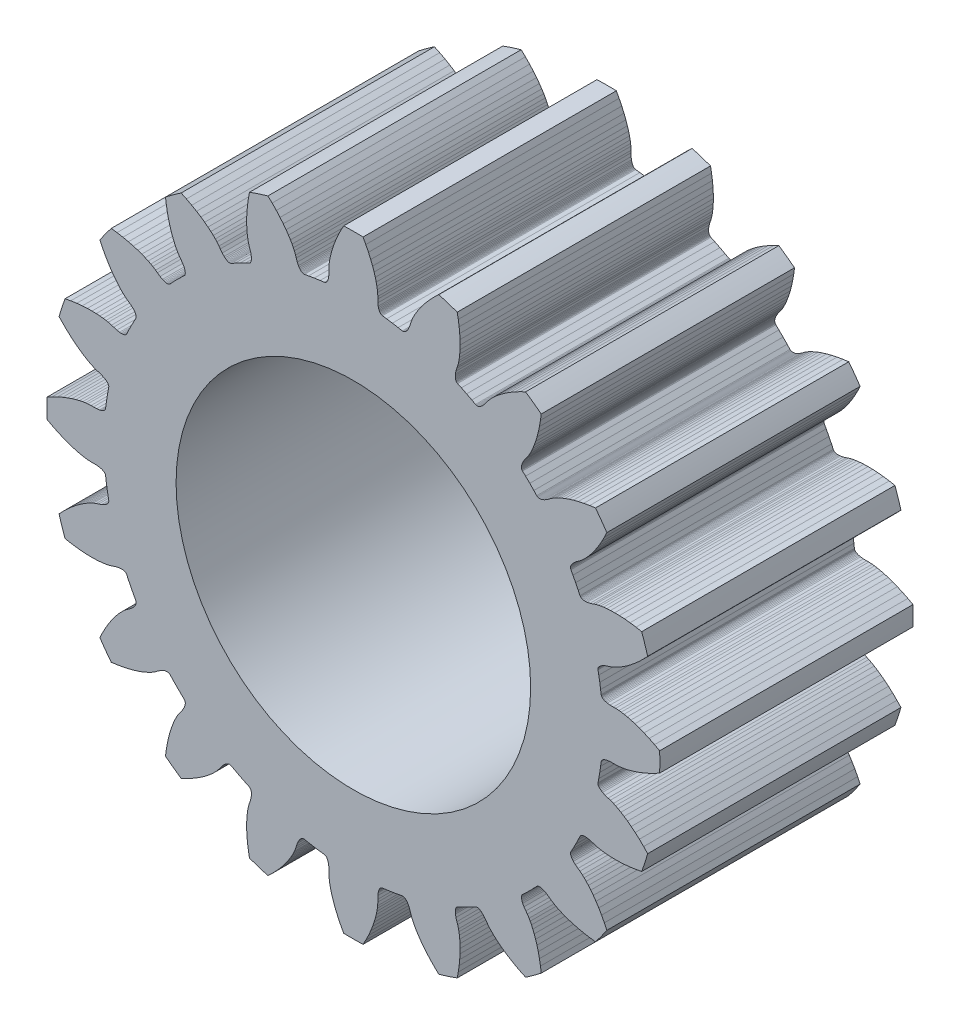
SolidWorks part; units mm, degrees
ref_plane "Front Plane" through (0, 0, 0) normal (0, 0, 1) x (1, 0, 0)
ref_plane "Top Plane" through (0, 0, 0) normal (0, 1, 0) x (1, 0, 0)
ref_plane "Right Plane" through (0, 0, 0) normal (1, 0, 0) x (0, 0, -1)
sketch "Model" plane through (0, 0, 0) normal (0, 0, 1) x (1, 0, 0)
  line L0 (11.4619, 3.2074) -> (11.2915, 3.0419)
  line L1 (11.2915, 3.0419) -> (11.1273, 2.8952)
  line L2 (11.1273, 2.8952) -> (10.9714, 2.7672)
  line L3 (10.9714, 2.7672) -> (10.8244, 2.6566)
  line L4 (10.8244, 2.6566) -> (10.6885, 2.5629)
  line L5 (10.6885, 2.5629) -> (10.5634, 2.4842)
  line L6 (10.5634, 2.4842) -> (10.4513, 2.42)
  line L7 (10.4513, 2.42) -> (10.3515, 2.3683)
  line L8 (10.3515, 2.3683) -> (10.268, 2.3294)
  line L9 (10.268, 2.3294) -> (10.146, 2.2812)
  line L10 (10.146, 2.2812) -> (10.0579, 2.255)
  line L11 (10.0579, 2.255) -> (9.9378, 2.2137)
  line L12 (9.9378, 2.2137) -> (9.8388, 2.1672)
  line L13 (9.8388, 2.1672) -> (9.7973, 2.1425)
  line L14 (9.7973, 2.1425) -> (9.7611, 2.117)
  line L15 (9.7611, 2.117) -> (9.7303, 2.0911)
  line L16 (9.7303, 2.0911) -> (9.7049, 2.065)
  line L17 (9.7049, 2.065) -> (9.6848, 2.0388)
  line L18 (9.6848, 2.0388) -> (9.67, 2.0128)
  line L19 (9.67, 2.0128) -> (9.6606, 1.9871)
  line L20 (9.6606, 1.9871) -> (9.6565, 1.962)
  line L21 (9.6565, 1.962) -> (9.6587, 1.9318)
  line L22 (9.6587, 1.9318) -> (9.6899, 1.7686)
  line L23 (9.6899, 1.7686) -> (9.7287, 1.5409)
  line L24 (9.7287, 1.5409) -> (9.7622, 1.3123)
  line L25 (9.7622, 1.3123) -> (9.7829, 1.1474)
  line L26 (9.7829, 1.1474) -> (9.7901, 1.118)
  line L27 (9.7901, 1.118) -> (9.8018, 1.0954)
  line L28 (9.8018, 1.0954) -> (9.8187, 1.0739)
  line L29 (9.8187, 1.0739) -> (9.8408, 1.0537)
  line L30 (9.8408, 1.0537) -> (9.868, 1.035)
  line L31 (9.868, 1.035) -> (9.9003, 1.018)
  line L32 (9.9003, 1.018) -> (9.9376, 1.0029)
  line L33 (9.9376, 1.0029) -> (9.9798, 0.9899)
  line L34 (9.9798, 0.9899) -> (10.0269, 0.9792)
  line L35 (10.0269, 0.9792) -> (10.1355, 0.9655)
  line L36 (10.1355, 0.9655) -> (10.2625, 0.9634)
  line L37 (10.2625, 0.9634) -> (10.3543, 0.9657)
  line L38 (10.3543, 0.9657) -> (10.4853, 0.9576)
  line L39 (10.4853, 0.9576) -> (10.5767, 0.9464)
  line L40 (10.5767, 0.9464) -> (10.6876, 0.9281)
  line L41 (10.6876, 0.9281) -> (10.814, 0.9017)
  line L42 (10.814, 0.9017) -> (10.9573, 0.8655)
  line L43 (10.9573, 0.8655) -> (11.1155, 0.8184)
  line L44 (11.1155, 0.8184) -> (11.2895, 0.7586)
  line L45 (11.2895, 0.7586) -> (11.4774, 0.685)
  line L46 (11.4774, 0.685) -> (11.6789, 0.5963)
  line L47 (11.6789, 0.5963) -> (11.8921, 0.4915)
  line L48 (11.8921, 0.4915) -> (12.094, 0.382)
  line L49 (12.094, -0.382) -> (11.8921, -0.4915)
  line L50 (11.8921, -0.4915) -> (11.6789, -0.5963)
  line L51 (11.6789, -0.5963) -> (11.4774, -0.685)
  line L52 (11.4774, -0.685) -> (11.2895, -0.7586)
  line L53 (11.2895, -0.7586) -> (11.1155, -0.8184)
  line L54 (11.1155, -0.8184) -> (10.9573, -0.8655)
  line L55 (10.9573, -0.8655) -> (10.814, -0.9017)
  line L56 (10.814, -0.9017) -> (10.6876, -0.9281)
  line L57 (10.6876, -0.9281) -> (10.5767, -0.9464)
  line L58 (10.5767, -0.9464) -> (10.4853, -0.9576)
  line L59 (10.4853, -0.9576) -> (10.3543, -0.9657)
  line L60 (10.3543, -0.9657) -> (10.2625, -0.9634)
  line L61 (10.2625, -0.9634) -> (10.1355, -0.9655)
  line L62 (10.1355, -0.9655) -> (10.0269, -0.9792)
  line L63 (10.0269, -0.9792) -> (9.9798, -0.9899)
  line L64 (9.9798, -0.9899) -> (9.9376, -1.0029)
  line L65 (9.9376, -1.0029) -> (9.9003, -1.018)
  line L66 (9.9003, -1.018) -> (9.868, -1.035)
  line L67 (9.868, -1.035) -> (9.8408, -1.0537)
  line L68 (9.8408, -1.0537) -> (9.8187, -1.0739)
  line L69 (9.8187, -1.0739) -> (9.8018, -1.0954)
  line L70 (9.8018, -1.0954) -> (9.7901, -1.118)
  line L71 (9.7901, -1.118) -> (9.7829, -1.1474)
  line L72 (9.7829, -1.1474) -> (9.7622, -1.3123)
  line L73 (9.7622, -1.3123) -> (9.7287, -1.5409)
  line L74 (9.7287, -1.5409) -> (9.6899, -1.7686)
  line L75 (9.6899, -1.7686) -> (9.6587, -1.9318)
  line L76 (9.6587, -1.9318) -> (9.6565, -1.962)
  line L77 (9.6565, -1.962) -> (9.6606, -1.9871)
  line L78 (9.6606, -1.9871) -> (9.67, -2.0128)
  line L79 (9.67, -2.0128) -> (9.6848, -2.0388)
  line L80 (9.6848, -2.0388) -> (9.7049, -2.065)
  line L81 (9.7049, -2.065) -> (9.7303, -2.0911)
  line L82 (9.7303, -2.0911) -> (9.7611, -2.117)
  line L83 (9.7611, -2.117) -> (9.7973, -2.1425)
  line L84 (9.7973, -2.1425) -> (9.8388, -2.1672)
  line L85 (9.8388, -2.1672) -> (9.9378, -2.2137)
  line L86 (9.9378, -2.2137) -> (10.0579, -2.255)
  line L87 (10.0579, -2.255) -> (10.146, -2.2812)
  line L88 (10.146, -2.2812) -> (10.268, -2.3294)
  line L89 (10.268, -2.3294) -> (10.3515, -2.3683)
  line L90 (10.3515, -2.3683) -> (10.4513, -2.42)
  line L91 (10.4513, -2.42) -> (10.5634, -2.4842)
  line L92 (10.5634, -2.4842) -> (10.6885, -2.5629)
  line L93 (10.6885, -2.5629) -> (10.8244, -2.6566)
  line L94 (10.8244, -2.6566) -> (10.9714, -2.7672)
  line L95 (10.9714, -2.7672) -> (11.1273, -2.8952)
  line L96 (11.1273, -2.8952) -> (11.2915, -3.0419)
  line L97 (11.2915, -3.0419) -> (11.4619, -3.2074)
  line L98 (11.4619, -3.2074) -> (11.6201, -3.374)
  line L99 (11.384, -4.1005) -> (11.1581, -4.1423)
  line L100 (11.1581, -4.1423) -> (10.923, -4.1761)
  line L101 (10.923, -4.1761) -> (10.7039, -4.1982)
  line L102 (10.7039, -4.1982) -> (10.5026, -4.2101)
  line L103 (10.5026, -4.2101) -> (10.3186, -4.2132)
  line L104 (10.3186, -4.2132) -> (10.1535, -4.2091)
  line L105 (10.1535, -4.2091) -> (10.0061, -4.1993)
  line L106 (10.0061, -4.1993) -> (9.8778, -4.1853)
  line L107 (9.8778, -4.1853) -> (9.7666, -4.1684)
  line L108 (9.7666, -4.1684) -> (9.6762, -4.1508)
  line L109 (9.6762, -4.1508) -> (9.5491, -4.1181)
  line L110 (9.5491, -4.1181) -> (9.4625, -4.0876)
  line L111 (9.4625, -4.0876) -> (9.3411, -4.0503)
  line L112 (9.3411, -4.0503) -> (9.2336, -4.0298)
  line L113 (9.2336, -4.0298) -> (9.1855, -4.0254)
  line L114 (9.1855, -4.0254) -> (9.1413, -4.0247)
  line L115 (9.1413, -4.0247) -> (9.1011, -4.0276)
  line L116 (9.1011, -4.0276) -> (9.0652, -4.0338)
  line L117 (9.0652, -4.0338) -> (9.0335, -4.0431)
  line L118 (9.0335, -4.0431) -> (9.0063, -4.0555)
  line L119 (9.0063, -4.0555) -> (8.9836, -4.0708)
  line L120 (8.9836, -4.0708) -> (8.9655, -4.0886)
  line L121 (8.9655, -4.0886) -> (8.9496, -4.1144)
  line L122 (8.9496, -4.1144) -> (8.8789, -4.2648)
  line L123 (8.8789, -4.2648) -> (8.7764, -4.4718)
  line L124 (8.7764, -4.4718) -> (8.6692, -4.6764)
  line L125 (8.6692, -4.6764) -> (8.589, -4.822)
  line L126 (8.589, -4.822) -> (8.5775, -4.85)
  line L127 (8.5775, -4.85) -> (8.5737, -4.8751)
  line L128 (8.5737, -4.8751) -> (8.5747, -4.9024)
  line L129 (8.5747, -4.9024) -> (8.5807, -4.9318)
  line L130 (8.5807, -4.9318) -> (8.5917, -4.9629)
  line L131 (8.5917, -4.9629) -> (8.6079, -4.9956)
  line L132 (8.6079, -4.9956) -> (8.6292, -5.0298)
  line L133 (8.6292, -5.0298) -> (8.6557, -5.0651)
  line L134 (8.6557, -5.0651) -> (8.6875, -5.1015)
  line L135 (8.6875, -5.1015) -> (8.7673, -5.1763)
  line L136 (8.7673, -5.1763) -> (8.8688, -5.2527)
  line L137 (8.8688, -5.2527) -> (8.9445, -5.3048)
  line L138 (8.9445, -5.3048) -> (9.0456, -5.3884)
  line L139 (9.0456, -5.3884) -> (9.113, -5.4512)
  line L140 (9.113, -5.4512) -> (9.192, -5.5312)
  line L141 (9.192, -5.5312) -> (9.2787, -5.6269)
  line L142 (9.2787, -5.6269) -> (9.3734, -5.7403)
  line L143 (9.3734, -5.7403) -> (9.4737, -5.8715)
  line L144 (9.4737, -5.8715) -> (9.5793, -6.0221)
  line L145 (9.5793, -6.0221) -> (9.688, -6.192)
  line L146 (9.688, -6.192) -> (9.7989, -6.3823)
  line L147 (9.7989, -6.3823) -> (9.9098, -6.5923)
  line L148 (9.9098, -6.5923) -> (10.0087, -6.7996)
  line L149 (9.5597, -7.4177) -> (9.332, -7.3876)
  line L150 (9.332, -7.3876) -> (9.0979, -7.3471)
  line L151 (9.0979, -7.3471) -> (8.8827, -7.3004)
  line L152 (8.8827, -7.3004) -> (8.6875, -7.2495)
  line L153 (8.6875, -7.2495) -> (8.5116, -7.1956)
  line L154 (8.5116, -7.1956) -> (8.3559, -7.1407)
  line L155 (8.3559, -7.1407) -> (8.2187, -7.0858)
  line L156 (8.2187, -7.0858) -> (8.101, -7.0329)
  line L157 (8.101, -7.0329) -> (8.0005, -6.9825)
  line L158 (8.0005, -6.9825) -> (7.9199, -6.9378)
  line L159 (7.9199, -6.9378) -> (7.8092, -6.8674)
  line L160 (7.8092, -6.8674) -> (7.7362, -6.8116)
  line L161 (7.7362, -6.8116) -> (7.6322, -6.7386)
  line L162 (7.6322, -6.7386) -> (7.5364, -6.6859)
  line L163 (7.5364, -6.6859) -> (7.492, -6.6669)
  line L164 (7.492, -6.6669) -> (7.4502, -6.6525)
  line L165 (7.4502, -6.6525) -> (7.4111, -6.6428)
  line L166 (7.4111, -6.6428) -> (7.375, -6.6376)
  line L167 (7.375, -6.6376) -> (7.342, -6.6368)
  line L168 (7.342, -6.6368) -> (7.3122, -6.6401)
  line L169 (7.3122, -6.6401) -> (7.286, -6.6476)
  line L170 (7.286, -6.6476) -> (7.2632, -6.659)
  line L171 (7.2632, -6.659) -> (7.2401, -6.6786)
  line L172 (7.2401, -6.6786) -> (7.1264, -6.7998)
  line L173 (7.1264, -6.7998) -> (6.965, -6.965)
  line L174 (6.965, -6.965) -> (6.7998, -7.1264)
  line L175 (6.7998, -7.1264) -> (6.6786, -7.2401)
  line L176 (6.6786, -7.2401) -> (6.659, -7.2632)
  line L177 (6.659, -7.2632) -> (6.6476, -7.286)
  line L178 (6.6476, -7.286) -> (6.6401, -7.3122)
  line L179 (6.6401, -7.3122) -> (6.6368, -7.342)
  line L180 (6.6368, -7.342) -> (6.6376, -7.375)
  line L181 (6.6376, -7.375) -> (6.6428, -7.4111)
  line L182 (6.6428, -7.4111) -> (6.6525, -7.4502)
  line L183 (6.6525, -7.4502) -> (6.6669, -7.492)
  line L184 (6.6669, -7.492) -> (6.6859, -7.5364)
  line L185 (6.6859, -7.5364) -> (6.7386, -7.6322)
  line L186 (6.7386, -7.6322) -> (6.8116, -7.7362)
  line L187 (6.8116, -7.7362) -> (6.8674, -7.8092)
  line L188 (6.8674, -7.8092) -> (6.9378, -7.9199)
  line L189 (6.9378, -7.9199) -> (6.9825, -8.0005)
  line L190 (6.9825, -8.0005) -> (7.0329, -8.101)
  line L191 (7.0329, -8.101) -> (7.0858, -8.2187)
  line L192 (7.0858, -8.2187) -> (7.1407, -8.3559)
  line L193 (7.1407, -8.3559) -> (7.1956, -8.5116)
  line L194 (7.1956, -8.5116) -> (7.2495, -8.6875)
  line L195 (7.2495, -8.6875) -> (7.3004, -8.8827)
  line L196 (7.3004, -8.8827) -> (7.3471, -9.0979)
  line L197 (7.3471, -9.0979) -> (7.3876, -9.332)
  line L198 (7.3876, -9.332) -> (7.4177, -9.5597)
  line L199 (6.7996, -10.0087) -> (6.5923, -9.9098)
  line L200 (6.5923, -9.9098) -> (6.3823, -9.7989)
  line L201 (6.3823, -9.7989) -> (6.192, -9.688)
  line L202 (6.192, -9.688) -> (6.0221, -9.5793)
  line L203 (6.0221, -9.5793) -> (5.8715, -9.4737)
  line L204 (5.8715, -9.4737) -> (5.7403, -9.3734)
  line L205 (5.7403, -9.3734) -> (5.6269, -9.2787)
  line L206 (5.6269, -9.2787) -> (5.5312, -9.192)
  line L207 (5.5312, -9.192) -> (5.4512, -9.113)
  line L208 (5.4512, -9.113) -> (5.3884, -9.0456)
  line L209 (5.3884, -9.0456) -> (5.3048, -8.9445)
  line L210 (5.3048, -8.9445) -> (5.2527, -8.8688)
  line L211 (5.2527, -8.8688) -> (5.1763, -8.7673)
  line L212 (5.1763, -8.7673) -> (5.1015, -8.6875)
  line L213 (5.1015, -8.6875) -> (5.0651, -8.6557)
  line L214 (5.0651, -8.6557) -> (5.0298, -8.6292)
  line L215 (5.0298, -8.6292) -> (4.9956, -8.6079)
  line L216 (4.9956, -8.6079) -> (4.9629, -8.5917)
  line L217 (4.9629, -8.5917) -> (4.9318, -8.5807)
  line L218 (4.9318, -8.5807) -> (4.9024, -8.5747)
  line L219 (4.9024, -8.5747) -> (4.8751, -8.5737)
  line L220 (4.8751, -8.5737) -> (4.85, -8.5775)
  line L221 (4.85, -8.5775) -> (4.822, -8.589)
  line L222 (4.822, -8.589) -> (4.6764, -8.6692)
  line L223 (4.6764, -8.6692) -> (4.4718, -8.7764)
  line L224 (4.4718, -8.7764) -> (4.2648, -8.8789)
  line L225 (4.2648, -8.8789) -> (4.1144, -8.9496)
  line L226 (4.1144, -8.9496) -> (4.0886, -8.9655)
  line L227 (4.0886, -8.9655) -> (4.0708, -8.9836)
  line L228 (4.0708, -8.9836) -> (4.0555, -9.0063)
  line L229 (4.0555, -9.0063) -> (4.0431, -9.0335)
  line L230 (4.0431, -9.0335) -> (4.0338, -9.0652)
  line L231 (4.0338, -9.0652) -> (4.0276, -9.1011)
  line L232 (4.0276, -9.1011) -> (4.0247, -9.1413)
  line L233 (4.0247, -9.1413) -> (4.0254, -9.1855)
  line L234 (4.0254, -9.1855) -> (4.0298, -9.2336)
  line L235 (4.0298, -9.2336) -> (4.0503, -9.3411)
  line L236 (4.0503, -9.3411) -> (4.0876, -9.4625)
  line L237 (4.0876, -9.4625) -> (4.1181, -9.5491)
  line L238 (4.1181, -9.5491) -> (4.1508, -9.6762)
  line L239 (4.1508, -9.6762) -> (4.1684, -9.7666)
  line L240 (4.1684, -9.7666) -> (4.1853, -9.8778)
  line L241 (4.1853, -9.8778) -> (4.1993, -10.0061)
  line L242 (4.1993, -10.0061) -> (4.2091, -10.1535)
  line L243 (4.2091, -10.1535) -> (4.2132, -10.3186)
  line L244 (4.2132, -10.3186) -> (4.2101, -10.5026)
  line L245 (4.2101, -10.5026) -> (4.1982, -10.7039)
  line L246 (4.1982, -10.7039) -> (4.1761, -10.923)
  line L247 (4.1761, -10.923) -> (4.1423, -11.1581)
  line L248 (4.1423, -11.1581) -> (4.1005, -11.384)
  line L249 (3.374, -11.6201) -> (3.2074, -11.4619)
  line L250 (3.2074, -11.4619) -> (3.0419, -11.2915)
  line L251 (3.0419, -11.2915) -> (2.8952, -11.1273)
  line L252 (2.8952, -11.1273) -> (2.7672, -10.9714)
  line L253 (2.7672, -10.9714) -> (2.6566, -10.8244)
  line L254 (2.6566, -10.8244) -> (2.5629, -10.6885)
  line L255 (2.5629, -10.6885) -> (2.4842, -10.5634)
  line L256 (2.4842, -10.5634) -> (2.42, -10.4513)
  line L257 (2.42, -10.4513) -> (2.3683, -10.3515)
  line L258 (2.3683, -10.3515) -> (2.3294, -10.268)
  line L259 (2.3294, -10.268) -> (2.2812, -10.146)
  line L260 (2.2812, -10.146) -> (2.255, -10.0579)
  line L261 (2.255, -10.0579) -> (2.2137, -9.9378)
  line L262 (2.2137, -9.9378) -> (2.1672, -9.8388)
  line L263 (2.1672, -9.8388) -> (2.1425, -9.7973)
  line L264 (2.1425, -9.7973) -> (2.117, -9.7611)
  line L265 (2.117, -9.7611) -> (2.0911, -9.7303)
  line L266 (2.0911, -9.7303) -> (2.065, -9.7049)
  line L267 (2.065, -9.7049) -> (2.0388, -9.6848)
  line L268 (2.0388, -9.6848) -> (2.0128, -9.67)
  line L269 (2.0128, -9.67) -> (1.9871, -9.6606)
  line L270 (1.9871, -9.6606) -> (1.962, -9.6565)
  line L271 (1.962, -9.6565) -> (1.9318, -9.6587)
  line L272 (1.9318, -9.6587) -> (1.7686, -9.6899)
  line L273 (1.7686, -9.6899) -> (1.5409, -9.7287)
  line L274 (1.5409, -9.7287) -> (1.3123, -9.7622)
  line L275 (1.3123, -9.7622) -> (1.1474, -9.7829)
  line L276 (1.1474, -9.7829) -> (1.118, -9.7901)
  line L277 (1.118, -9.7901) -> (1.0954, -9.8018)
  line L278 (1.0954, -9.8018) -> (1.0739, -9.8187)
  line L279 (1.0739, -9.8187) -> (1.0537, -9.8408)
  line L280 (1.0537, -9.8408) -> (1.035, -9.868)
  line L281 (1.035, -9.868) -> (1.018, -9.9003)
  line L282 (1.018, -9.9003) -> (1.0029, -9.9376)
  line L283 (1.0029, -9.9376) -> (0.9899, -9.9798)
  line L284 (0.9899, -9.9798) -> (0.9792, -10.0269)
  line L285 (0.9792, -10.0269) -> (0.9655, -10.1355)
  line L286 (0.9655, -10.1355) -> (0.9634, -10.2625)
  line L287 (0.9634, -10.2625) -> (0.9657, -10.3543)
  line L288 (0.9657, -10.3543) -> (0.9576, -10.4853)
  line L289 (0.9576, -10.4853) -> (0.9464, -10.5767)
  line L290 (0.9464, -10.5767) -> (0.9281, -10.6876)
  line L291 (0.9281, -10.6876) -> (0.9017, -10.814)
  line L292 (0.9017, -10.814) -> (0.8655, -10.9573)
  line L293 (0.8655, -10.9573) -> (0.8184, -11.1155)
  line L294 (0.8184, -11.1155) -> (0.7586, -11.2895)
  line L295 (0.7586, -11.2895) -> (0.685, -11.4774)
  line L296 (0.685, -11.4774) -> (0.5963, -11.6789)
  line L297 (0.5963, -11.6789) -> (0.4915, -11.8921)
  line L298 (0.4915, -11.8921) -> (0.382, -12.094)
  line L299 (-0.382, -12.094) -> (-0.4915, -11.8921)
  line L300 (-0.4915, -11.8921) -> (-0.5963, -11.6789)
  line L301 (-0.5963, -11.6789) -> (-0.685, -11.4774)
  line L302 (-0.685, -11.4774) -> (-0.7586, -11.2895)
  line L303 (-0.7586, -11.2895) -> (-0.8184, -11.1155)
  line L304 (-0.8184, -11.1155) -> (-0.8655, -10.9573)
  line L305 (-0.8655, -10.9573) -> (-0.9017, -10.814)
  line L306 (-0.9017, -10.814) -> (-0.9281, -10.6876)
  line L307 (-0.9281, -10.6876) -> (-0.9464, -10.5767)
  line L308 (-0.9464, -10.5767) -> (-0.9576, -10.4853)
  line L309 (-0.9576, -10.4853) -> (-0.9657, -10.3543)
  line L310 (-0.9657, -10.3543) -> (-0.9634, -10.2625)
  line L311 (-0.9634, -10.2625) -> (-0.9655, -10.1355)
  line L312 (-0.9655, -10.1355) -> (-0.9792, -10.0269)
  line L313 (-0.9792, -10.0269) -> (-0.9899, -9.9798)
  line L314 (-0.9899, -9.9798) -> (-1.0029, -9.9376)
  line L315 (-1.0029, -9.9376) -> (-1.018, -9.9003)
  line L316 (-1.018, -9.9003) -> (-1.035, -9.868)
  line L317 (-1.035, -9.868) -> (-1.0537, -9.8408)
  line L318 (-1.0537, -9.8408) -> (-1.0739, -9.8187)
  line L319 (-1.0739, -9.8187) -> (-1.0954, -9.8018)
  line L320 (-1.0954, -9.8018) -> (-1.118, -9.7901)
  line L321 (-1.118, -9.7901) -> (-1.1474, -9.7829)
  line L322 (-1.1474, -9.7829) -> (-1.3123, -9.7622)
  line L323 (-1.3123, -9.7622) -> (-1.5409, -9.7287)
  line L324 (-1.5409, -9.7287) -> (-1.7686, -9.6899)
  line L325 (-1.7686, -9.6899) -> (-1.9318, -9.6587)
  line L326 (-1.9318, -9.6587) -> (-1.962, -9.6565)
  line L327 (-1.962, -9.6565) -> (-1.9871, -9.6606)
  line L328 (-1.9871, -9.6606) -> (-2.0128, -9.67)
  line L329 (-2.0128, -9.67) -> (-2.0388, -9.6848)
  line L330 (-2.0388, -9.6848) -> (-2.065, -9.7049)
  line L331 (-2.065, -9.7049) -> (-2.0911, -9.7303)
  line L332 (-2.0911, -9.7303) -> (-2.117, -9.7611)
  line L333 (-2.117, -9.7611) -> (-2.1425, -9.7973)
  line L334 (-2.1425, -9.7973) -> (-2.1672, -9.8388)
  line L335 (-2.1672, -9.8388) -> (-2.2137, -9.9378)
  line L336 (-2.2137, -9.9378) -> (-2.255, -10.0579)
  line L337 (-2.255, -10.0579) -> (-2.2812, -10.146)
  line L338 (-2.2812, -10.146) -> (-2.3294, -10.268)
  line L339 (-2.3294, -10.268) -> (-2.3683, -10.3515)
  line L340 (-2.3683, -10.3515) -> (-2.42, -10.4513)
  line L341 (-2.42, -10.4513) -> (-2.4842, -10.5634)
  line L342 (-2.4842, -10.5634) -> (-2.5629, -10.6885)
  line L343 (-2.5629, -10.6885) -> (-2.6566, -10.8244)
  line L344 (-2.6566, -10.8244) -> (-2.7672, -10.9714)
  line L345 (-2.7672, -10.9714) -> (-2.8952, -11.1273)
  line L346 (-2.8952, -11.1273) -> (-3.0419, -11.2915)
  line L347 (-3.0419, -11.2915) -> (-3.2074, -11.4619)
  line L348 (-3.2074, -11.4619) -> (-3.374, -11.6201)
  line L349 (-4.1005, -11.384) -> (-4.1423, -11.1581)
  line L350 (-4.1423, -11.1581) -> (-4.1761, -10.923)
  line L351 (-4.1761, -10.923) -> (-4.1982, -10.7039)
  line L352 (-4.1982, -10.7039) -> (-4.2101, -10.5026)
  line L353 (-4.2101, -10.5026) -> (-4.2132, -10.3186)
  line L354 (-4.2132, -10.3186) -> (-4.2091, -10.1535)
  line L355 (-4.2091, -10.1535) -> (-4.1993, -10.0061)
  line L356 (-4.1993, -10.0061) -> (-4.1853, -9.8778)
  line L357 (-4.1853, -9.8778) -> (-4.1684, -9.7666)
  line L358 (-4.1684, -9.7666) -> (-4.1508, -9.6762)
  line L359 (-4.1508, -9.6762) -> (-4.1181, -9.5491)
  line L360 (-4.1181, -9.5491) -> (-4.0876, -9.4625)
  line L361 (-4.0876, -9.4625) -> (-4.0503, -9.3411)
  line L362 (-4.0503, -9.3411) -> (-4.0298, -9.2336)
  line L363 (-4.0298, -9.2336) -> (-4.0254, -9.1855)
  line L364 (-4.0254, -9.1855) -> (-4.0247, -9.1413)
  line L365 (-4.0247, -9.1413) -> (-4.0276, -9.1011)
  line L366 (-4.0276, -9.1011) -> (-4.0338, -9.0652)
  line L367 (-4.0338, -9.0652) -> (-4.0431, -9.0335)
  line L368 (-4.0431, -9.0335) -> (-4.0555, -9.0063)
  line L369 (-4.0555, -9.0063) -> (-4.0708, -8.9836)
  line L370 (-4.0708, -8.9836) -> (-4.0886, -8.9655)
  line L371 (-4.0886, -8.9655) -> (-4.1144, -8.9496)
  line L372 (-4.1144, -8.9496) -> (-4.2648, -8.8789)
  line L373 (-4.2648, -8.8789) -> (-4.4718, -8.7764)
  line L374 (-4.4718, -8.7764) -> (-4.6764, -8.6692)
  line L375 (-4.6764, -8.6692) -> (-4.822, -8.589)
  line L376 (-4.822, -8.589) -> (-4.85, -8.5775)
  line L377 (-4.85, -8.5775) -> (-4.8751, -8.5737)
  line L378 (-4.8751, -8.5737) -> (-4.9024, -8.5747)
  line L379 (-4.9024, -8.5747) -> (-4.9318, -8.5807)
  line L380 (-4.9318, -8.5807) -> (-4.9629, -8.5917)
  line L381 (-4.9629, -8.5917) -> (-4.9956, -8.6079)
  line L382 (-4.9956, -8.6079) -> (-5.0298, -8.6292)
  line L383 (-5.0298, -8.6292) -> (-5.0651, -8.6557)
  line L384 (-5.0651, -8.6557) -> (-5.1015, -8.6875)
  line L385 (-5.1015, -8.6875) -> (-5.1763, -8.7673)
  line L386 (-5.1763, -8.7673) -> (-5.2527, -8.8688)
  line L387 (-5.2527, -8.8688) -> (-5.3048, -8.9445)
  line L388 (-5.3048, -8.9445) -> (-5.3884, -9.0456)
  line L389 (-5.3884, -9.0456) -> (-5.4512, -9.113)
  line L390 (-5.4512, -9.113) -> (-5.5312, -9.192)
  line L391 (-5.5312, -9.192) -> (-5.6269, -9.2787)
  line L392 (-5.6269, -9.2787) -> (-5.7403, -9.3734)
  line L393 (-5.7403, -9.3734) -> (-5.8715, -9.4737)
  line L394 (-5.8715, -9.4737) -> (-6.0221, -9.5793)
  line L395 (-6.0221, -9.5793) -> (-6.192, -9.688)
  line L396 (-6.192, -9.688) -> (-6.3823, -9.7989)
  line L397 (-6.3823, -9.7989) -> (-6.5923, -9.9098)
  line L398 (-6.5923, -9.9098) -> (-6.7996, -10.0087)
  line L399 (-7.4177, -9.5597) -> (-7.3876, -9.332)
  line L400 (-7.3876, -9.332) -> (-7.3471, -9.0979)
  line L401 (-7.3471, -9.0979) -> (-7.3004, -8.8827)
  line L402 (-7.3004, -8.8827) -> (-7.2495, -8.6875)
  line L403 (-7.2495, -8.6875) -> (-7.1956, -8.5116)
  line L404 (-7.1956, -8.5116) -> (-7.1407, -8.3559)
  line L405 (-7.1407, -8.3559) -> (-7.0858, -8.2187)
  line L406 (-7.0858, -8.2187) -> (-7.0329, -8.101)
  line L407 (-7.0329, -8.101) -> (-6.9825, -8.0005)
  line L408 (-6.9825, -8.0005) -> (-6.9378, -7.9199)
  line L409 (-6.9378, -7.9199) -> (-6.8674, -7.8092)
  line L410 (-6.8674, -7.8092) -> (-6.8116, -7.7362)
  line L411 (-6.8116, -7.7362) -> (-6.7386, -7.6322)
  line L412 (-6.7386, -7.6322) -> (-6.6859, -7.5364)
  line L413 (-6.6859, -7.5364) -> (-6.6669, -7.492)
  line L414 (-6.6669, -7.492) -> (-6.6525, -7.4502)
  line L415 (-6.6525, -7.4502) -> (-6.6428, -7.4111)
  line L416 (-6.6428, -7.4111) -> (-6.6376, -7.375)
  line L417 (-6.6376, -7.375) -> (-6.6368, -7.342)
  line L418 (-6.6368, -7.342) -> (-6.6401, -7.3122)
  line L419 (-6.6401, -7.3122) -> (-6.6476, -7.286)
  line L420 (-6.6476, -7.286) -> (-6.659, -7.2632)
  line L421 (-6.659, -7.2632) -> (-6.6786, -7.2401)
  line L422 (-6.6786, -7.2401) -> (-6.7998, -7.1264)
  line L423 (-6.7998, -7.1264) -> (-6.965, -6.965)
  line L424 (-6.965, -6.965) -> (-7.1264, -6.7998)
  line L425 (-7.1264, -6.7998) -> (-7.2401, -6.6786)
  line L426 (-7.2401, -6.6786) -> (-7.2632, -6.659)
  line L427 (-7.2632, -6.659) -> (-7.286, -6.6476)
  line L428 (-7.286, -6.6476) -> (-7.3122, -6.6401)
  line L429 (-7.3122, -6.6401) -> (-7.342, -6.6368)
  line L430 (-7.342, -6.6368) -> (-7.375, -6.6376)
  line L431 (-7.375, -6.6376) -> (-7.4111, -6.6428)
  line L432 (-7.4111, -6.6428) -> (-7.4502, -6.6525)
  line L433 (-7.4502, -6.6525) -> (-7.492, -6.6669)
  line L434 (-7.492, -6.6669) -> (-7.5364, -6.6859)
  line L435 (-7.5364, -6.6859) -> (-7.6322, -6.7386)
  line L436 (-7.6322, -6.7386) -> (-7.7362, -6.8116)
  line L437 (-7.7362, -6.8116) -> (-7.8092, -6.8674)
  line L438 (-7.8092, -6.8674) -> (-7.9199, -6.9378)
  line L439 (-7.9199, -6.9378) -> (-8.0005, -6.9825)
  line L440 (-8.0005, -6.9825) -> (-8.101, -7.0329)
  line L441 (-8.101, -7.0329) -> (-8.2187, -7.0858)
  line L442 (-8.2187, -7.0858) -> (-8.3559, -7.1407)
  line L443 (-8.3559, -7.1407) -> (-8.5116, -7.1956)
  line L444 (-8.5116, -7.1956) -> (-8.6875, -7.2495)
  line L445 (-8.6875, -7.2495) -> (-8.8827, -7.3004)
  line L446 (-8.8827, -7.3004) -> (-9.0979, -7.3471)
  line L447 (-9.0979, -7.3471) -> (-9.332, -7.3876)
  line L448 (-9.332, -7.3876) -> (-9.5597, -7.4177)
  line L449 (-10.0087, -6.7996) -> (-9.9098, -6.5923)
  line L450 (-9.9098, -6.5923) -> (-9.7989, -6.3823)
  line L451 (-9.7989, -6.3823) -> (-9.688, -6.192)
  line L452 (-9.688, -6.192) -> (-9.5793, -6.0221)
  line L453 (-9.5793, -6.0221) -> (-9.4737, -5.8715)
  line L454 (-9.4737, -5.8715) -> (-9.3734, -5.7403)
  line L455 (-9.3734, -5.7403) -> (-9.2787, -5.6269)
  line L456 (-9.2787, -5.6269) -> (-9.192, -5.5312)
  line L457 (-9.192, -5.5312) -> (-9.113, -5.4512)
  line L458 (-9.113, -5.4512) -> (-9.0456, -5.3884)
  line L459 (-9.0456, -5.3884) -> (-8.9445, -5.3048)
  line L460 (-8.9445, -5.3048) -> (-8.8688, -5.2527)
  line L461 (-8.8688, -5.2527) -> (-8.7673, -5.1763)
  line L462 (-8.7673, -5.1763) -> (-8.6875, -5.1015)
  line L463 (-8.6875, -5.1015) -> (-8.6557, -5.0651)
  line L464 (-8.6557, -5.0651) -> (-8.6292, -5.0298)
  line L465 (-8.6292, -5.0298) -> (-8.6079, -4.9956)
  line L466 (-8.6079, -4.9956) -> (-8.5917, -4.9629)
  line L467 (-8.5917, -4.9629) -> (-8.5807, -4.9318)
  line L468 (-8.5807, -4.9318) -> (-8.5747, -4.9024)
  line L469 (-8.5747, -4.9024) -> (-8.5737, -4.8751)
  line L470 (-8.5737, -4.8751) -> (-8.5775, -4.85)
  line L471 (-8.5775, -4.85) -> (-8.589, -4.822)
  line L472 (-8.589, -4.822) -> (-8.6692, -4.6764)
  line L473 (-8.6692, -4.6764) -> (-8.7764, -4.4718)
  line L474 (-8.7764, -4.4718) -> (-8.8789, -4.2648)
  line L475 (-8.8789, -4.2648) -> (-8.9496, -4.1144)
  line L476 (-8.9496, -4.1144) -> (-8.9655, -4.0886)
  line L477 (-8.9655, -4.0886) -> (-8.9836, -4.0708)
  line L478 (-8.9836, -4.0708) -> (-9.0063, -4.0555)
  line L479 (-9.0063, -4.0555) -> (-9.0335, -4.0431)
  line L480 (-9.0335, -4.0431) -> (-9.0652, -4.0338)
  line L481 (-9.0652, -4.0338) -> (-9.1011, -4.0276)
  line L482 (-9.1011, -4.0276) -> (-9.1413, -4.0247)
  line L483 (-9.1413, -4.0247) -> (-9.1855, -4.0254)
  line L484 (-9.1855, -4.0254) -> (-9.2336, -4.0298)
  line L485 (-9.2336, -4.0298) -> (-9.3411, -4.0503)
  line L486 (-9.3411, -4.0503) -> (-9.4625, -4.0876)
  line L487 (-9.4625, -4.0876) -> (-9.5491, -4.1181)
  line L488 (-9.5491, -4.1181) -> (-9.6762, -4.1508)
  line L489 (-9.6762, -4.1508) -> (-9.7666, -4.1684)
  line L490 (-9.7666, -4.1684) -> (-9.8778, -4.1853)
  line L491 (-9.8778, -4.1853) -> (-10.0061, -4.1993)
  line L492 (-10.0061, -4.1993) -> (-10.1535, -4.2091)
  line L493 (-10.1535, -4.2091) -> (-10.3186, -4.2132)
  line L494 (-10.3186, -4.2132) -> (-10.5026, -4.2101)
  line L495 (-10.5026, -4.2101) -> (-10.7039, -4.1982)
  line L496 (-10.7039, -4.1982) -> (-10.923, -4.1761)
  line L497 (-10.923, -4.1761) -> (-11.1581, -4.1423)
  line L498 (-11.1581, -4.1423) -> (-11.384, -4.1005)
  line L499 (-11.6201, -3.374) -> (-11.4619, -3.2074)
  line L500 (-11.4619, -3.2074) -> (-11.2915, -3.0419)
  line L501 (-11.2915, -3.0419) -> (-11.1273, -2.8952)
  line L502 (-11.1273, -2.8952) -> (-10.9714, -2.7672)
  line L503 (-10.9714, -2.7672) -> (-10.8244, -2.6566)
  line L504 (-10.8244, -2.6566) -> (-10.6885, -2.5629)
  line L505 (-10.6885, -2.5629) -> (-10.5634, -2.4842)
  line L506 (-10.5634, -2.4842) -> (-10.4513, -2.42)
  line L507 (-10.4513, -2.42) -> (-10.3515, -2.3683)
  line L508 (-10.3515, -2.3683) -> (-10.268, -2.3294)
  line L509 (-10.268, -2.3294) -> (-10.146, -2.2812)
  line L510 (-10.146, -2.2812) -> (-10.0579, -2.255)
  line L511 (-10.0579, -2.255) -> (-9.9378, -2.2137)
  line L512 (-9.9378, -2.2137) -> (-9.8388, -2.1672)
  line L513 (-9.8388, -2.1672) -> (-9.7973, -2.1425)
  line L514 (-9.7973, -2.1425) -> (-9.7611, -2.117)
  line L515 (-9.7611, -2.117) -> (-9.7303, -2.0911)
  line L516 (-9.7303, -2.0911) -> (-9.7049, -2.065)
  line L517 (-9.7049, -2.065) -> (-9.6848, -2.0388)
  line L518 (-9.6848, -2.0388) -> (-9.67, -2.0128)
  line L519 (-9.67, -2.0128) -> (-9.6606, -1.9871)
  line L520 (-9.6606, -1.9871) -> (-9.6565, -1.962)
  line L521 (-9.6565, -1.962) -> (-9.6587, -1.9318)
  line L522 (-9.6587, -1.9318) -> (-9.6899, -1.7686)
  line L523 (-9.6899, -1.7686) -> (-9.7287, -1.5409)
  line L524 (-9.7287, -1.5409) -> (-9.7622, -1.3123)
  line L525 (-9.7622, -1.3123) -> (-9.7829, -1.1474)
  line L526 (-9.7829, -1.1474) -> (-9.7901, -1.118)
  line L527 (-9.7901, -1.118) -> (-9.8018, -1.0954)
  line L528 (-9.8018, -1.0954) -> (-9.8187, -1.0739)
  line L529 (-9.8187, -1.0739) -> (-9.8408, -1.0537)
  line L530 (-9.8408, -1.0537) -> (-9.868, -1.035)
  line L531 (-9.868, -1.035) -> (-9.9003, -1.018)
  line L532 (-9.9003, -1.018) -> (-9.9376, -1.0029)
  line L533 (-9.9376, -1.0029) -> (-9.9798, -0.9899)
  line L534 (-9.9798, -0.9899) -> (-10.0269, -0.9792)
  line L535 (-10.0269, -0.9792) -> (-10.1355, -0.9655)
  line L536 (-10.1355, -0.9655) -> (-10.2625, -0.9634)
  line L537 (-10.2625, -0.9634) -> (-10.3543, -0.9657)
  line L538 (-10.3543, -0.9657) -> (-10.4853, -0.9576)
  line L539 (-10.4853, -0.9576) -> (-10.5767, -0.9464)
  line L540 (-10.5767, -0.9464) -> (-10.6876, -0.9281)
  line L541 (-10.6876, -0.9281) -> (-10.814, -0.9017)
  line L542 (-10.814, -0.9017) -> (-10.9573, -0.8655)
  line L543 (-10.9573, -0.8655) -> (-11.1155, -0.8184)
  line L544 (-11.1155, -0.8184) -> (-11.2895, -0.7586)
  line L545 (-11.2895, -0.7586) -> (-11.4774, -0.685)
  line L546 (-11.4774, -0.685) -> (-11.6789, -0.5963)
  line L547 (-11.6789, -0.5963) -> (-11.8921, -0.4915)
  line L548 (-11.8921, -0.4915) -> (-12.094, -0.382)
  line L549 (-12.094, 0.382) -> (-11.8921, 0.4915)
  line L550 (-11.8921, 0.4915) -> (-11.6789, 0.5963)
  line L551 (-11.6789, 0.5963) -> (-11.4774, 0.685)
  line L552 (-11.4774, 0.685) -> (-11.2895, 0.7586)
  line L553 (-11.2895, 0.7586) -> (-11.1155, 0.8184)
  line L554 (-11.1155, 0.8184) -> (-10.9573, 0.8655)
  line L555 (-10.9573, 0.8655) -> (-10.814, 0.9017)
  line L556 (-10.814, 0.9017) -> (-10.6876, 0.9281)
  line L557 (-10.6876, 0.9281) -> (-10.5767, 0.9464)
  line L558 (-10.5767, 0.9464) -> (-10.4853, 0.9576)
  line L559 (-10.4853, 0.9576) -> (-10.3543, 0.9657)
  line L560 (-10.3543, 0.9657) -> (-10.2625, 0.9634)
  line L561 (-10.2625, 0.9634) -> (-10.1355, 0.9655)
  line L562 (-10.1355, 0.9655) -> (-10.0269, 0.9792)
  line L563 (-10.0269, 0.9792) -> (-9.9798, 0.9899)
  line L564 (-9.9798, 0.9899) -> (-9.9376, 1.0029)
  line L565 (-9.9376, 1.0029) -> (-9.9003, 1.018)
  line L566 (-9.9003, 1.018) -> (-9.868, 1.035)
  line L567 (-9.868, 1.035) -> (-9.8408, 1.0537)
  line L568 (-9.8408, 1.0537) -> (-9.8187, 1.0739)
  line L569 (-9.8187, 1.0739) -> (-9.8018, 1.0954)
  line L570 (-9.8018, 1.0954) -> (-9.7901, 1.118)
  line L571 (-9.7901, 1.118) -> (-9.7829, 1.1474)
  line L572 (-9.7829, 1.1474) -> (-9.7622, 1.3123)
  line L573 (-9.7622, 1.3123) -> (-9.7287, 1.5409)
  line L574 (-9.7287, 1.5409) -> (-9.6899, 1.7686)
  line L575 (-9.6899, 1.7686) -> (-9.6587, 1.9318)
  line L576 (-9.6587, 1.9318) -> (-9.6565, 1.962)
  line L577 (-9.6565, 1.962) -> (-9.6606, 1.9871)
  line L578 (-9.6606, 1.9871) -> (-9.67, 2.0128)
  line L579 (-9.67, 2.0128) -> (-9.6848, 2.0388)
  line L580 (-9.6848, 2.0388) -> (-9.7049, 2.065)
  line L581 (-9.7049, 2.065) -> (-9.7303, 2.0911)
  line L582 (-9.7303, 2.0911) -> (-9.7611, 2.117)
  line L583 (-9.7611, 2.117) -> (-9.7973, 2.1425)
  line L584 (-9.7973, 2.1425) -> (-9.8388, 2.1672)
  line L585 (-9.8388, 2.1672) -> (-9.9378, 2.2137)
  line L586 (-9.9378, 2.2137) -> (-10.0579, 2.255)
  line L587 (-10.0579, 2.255) -> (-10.146, 2.2812)
  line L588 (-10.146, 2.2812) -> (-10.268, 2.3294)
  line L589 (-10.268, 2.3294) -> (-10.3515, 2.3683)
  line L590 (-10.3515, 2.3683) -> (-10.4513, 2.42)
  line L591 (-10.4513, 2.42) -> (-10.5634, 2.4842)
  line L592 (-10.5634, 2.4842) -> (-10.6885, 2.5629)
  line L593 (-10.6885, 2.5629) -> (-10.8244, 2.6566)
  line L594 (-10.8244, 2.6566) -> (-10.9714, 2.7672)
  line L595 (-10.9714, 2.7672) -> (-11.1273, 2.8952)
  line L596 (-11.1273, 2.8952) -> (-11.2915, 3.0419)
  line L597 (-11.2915, 3.0419) -> (-11.4619, 3.2074)
  line L598 (-11.4619, 3.2074) -> (-11.6201, 3.374)
  line L599 (-11.384, 4.1005) -> (-11.1581, 4.1423)
  line L600 (-11.1581, 4.1423) -> (-10.923, 4.1761)
  line L601 (-10.923, 4.1761) -> (-10.7039, 4.1982)
  line L602 (-10.7039, 4.1982) -> (-10.5026, 4.2101)
  line L603 (-10.5026, 4.2101) -> (-10.3186, 4.2132)
  line L604 (-10.3186, 4.2132) -> (-10.1535, 4.2091)
  line L605 (-10.1535, 4.2091) -> (-10.0061, 4.1993)
  line L606 (-10.0061, 4.1993) -> (-9.8778, 4.1853)
  line L607 (-9.8778, 4.1853) -> (-9.7666, 4.1684)
  line L608 (-9.7666, 4.1684) -> (-9.6762, 4.1508)
  line L609 (-9.6762, 4.1508) -> (-9.5491, 4.1181)
  line L610 (-9.5491, 4.1181) -> (-9.4625, 4.0876)
  line L611 (-9.4625, 4.0876) -> (-9.3411, 4.0503)
  line L612 (-9.3411, 4.0503) -> (-9.2336, 4.0298)
  line L613 (-9.2336, 4.0298) -> (-9.1855, 4.0254)
  line L614 (-9.1855, 4.0254) -> (-9.1413, 4.0247)
  line L615 (-9.1413, 4.0247) -> (-9.1011, 4.0276)
  line L616 (-9.1011, 4.0276) -> (-9.0652, 4.0338)
  line L617 (-9.0652, 4.0338) -> (-9.0335, 4.0431)
  line L618 (-9.0335, 4.0431) -> (-9.0063, 4.0555)
  line L619 (-9.0063, 4.0555) -> (-8.9836, 4.0708)
  line L620 (-8.9836, 4.0708) -> (-8.9655, 4.0886)
  line L621 (-8.9655, 4.0886) -> (-8.9496, 4.1144)
  line L622 (-8.9496, 4.1144) -> (-8.8789, 4.2648)
  line L623 (-8.8789, 4.2648) -> (-8.7764, 4.4718)
  line L624 (-8.7764, 4.4718) -> (-8.6692, 4.6764)
  line L625 (-8.6692, 4.6764) -> (-8.589, 4.822)
  line L626 (-8.589, 4.822) -> (-8.5775, 4.85)
  line L627 (-8.5775, 4.85) -> (-8.5737, 4.8751)
  line L628 (-8.5737, 4.8751) -> (-8.5747, 4.9024)
  line L629 (-8.5747, 4.9024) -> (-8.5807, 4.9318)
  line L630 (-8.5807, 4.9318) -> (-8.5917, 4.9629)
  line L631 (-8.5917, 4.9629) -> (-8.6079, 4.9956)
  line L632 (-8.6079, 4.9956) -> (-8.6292, 5.0298)
  line L633 (-8.6292, 5.0298) -> (-8.6557, 5.0651)
  line L634 (-8.6557, 5.0651) -> (-8.6875, 5.1015)
  line L635 (-8.6875, 5.1015) -> (-8.7673, 5.1763)
  line L636 (-8.7673, 5.1763) -> (-8.8688, 5.2527)
  line L637 (-8.8688, 5.2527) -> (-8.9445, 5.3048)
  line L638 (-8.9445, 5.3048) -> (-9.0456, 5.3884)
  line L639 (-9.0456, 5.3884) -> (-9.113, 5.4512)
  line L640 (-9.113, 5.4512) -> (-9.192, 5.5312)
  line L641 (-9.192, 5.5312) -> (-9.2787, 5.6269)
  line L642 (-9.2787, 5.6269) -> (-9.3734, 5.7403)
  line L643 (-9.3734, 5.7403) -> (-9.4737, 5.8715)
  line L644 (-9.4737, 5.8715) -> (-9.5793, 6.0221)
  line L645 (-9.5793, 6.0221) -> (-9.688, 6.192)
  line L646 (-9.688, 6.192) -> (-9.7989, 6.3823)
  line L647 (-9.7989, 6.3823) -> (-9.9098, 6.5923)
  line L648 (-9.9098, 6.5923) -> (-10.0087, 6.7996)
  line L649 (-9.5597, 7.4177) -> (-9.332, 7.3876)
  line L650 (-9.332, 7.3876) -> (-9.0979, 7.3471)
  line L651 (-9.0979, 7.3471) -> (-8.8827, 7.3004)
  line L652 (-8.8827, 7.3004) -> (-8.6875, 7.2495)
  line L653 (-8.6875, 7.2495) -> (-8.5116, 7.1956)
  line L654 (-8.5116, 7.1956) -> (-8.3559, 7.1407)
  line L655 (-8.3559, 7.1407) -> (-8.2187, 7.0858)
  line L656 (-8.2187, 7.0858) -> (-8.101, 7.0329)
  line L657 (-8.101, 7.0329) -> (-8.0005, 6.9825)
  line L658 (-8.0005, 6.9825) -> (-7.9199, 6.9378)
  line L659 (-7.9199, 6.9378) -> (-7.8092, 6.8674)
  line L660 (-7.8092, 6.8674) -> (-7.7362, 6.8116)
  line L661 (-7.7362, 6.8116) -> (-7.6322, 6.7386)
  line L662 (-7.6322, 6.7386) -> (-7.5364, 6.6859)
  line L663 (-7.5364, 6.6859) -> (-7.492, 6.6669)
  line L664 (-7.492, 6.6669) -> (-7.4502, 6.6525)
  line L665 (-7.4502, 6.6525) -> (-7.4111, 6.6428)
  line L666 (-7.4111, 6.6428) -> (-7.375, 6.6376)
  line L667 (-7.375, 6.6376) -> (-7.342, 6.6368)
  line L668 (-7.342, 6.6368) -> (-7.3122, 6.6401)
  line L669 (-7.3122, 6.6401) -> (-7.286, 6.6476)
  line L670 (-7.286, 6.6476) -> (-7.2632, 6.659)
  line L671 (-7.2632, 6.659) -> (-7.2401, 6.6786)
  line L672 (-7.2401, 6.6786) -> (-7.1264, 6.7998)
  line L673 (-7.1264, 6.7998) -> (-6.965, 6.965)
  line L674 (-6.965, 6.965) -> (-6.7998, 7.1264)
  line L675 (-6.7998, 7.1264) -> (-6.6786, 7.2401)
  line L676 (-6.6786, 7.2401) -> (-6.659, 7.2632)
  line L677 (-6.659, 7.2632) -> (-6.6476, 7.286)
  line L678 (-6.6476, 7.286) -> (-6.6401, 7.3122)
  line L679 (-6.6401, 7.3122) -> (-6.6368, 7.342)
  line L680 (-6.6368, 7.342) -> (-6.6376, 7.375)
  line L681 (-6.6376, 7.375) -> (-6.6428, 7.4111)
  line L682 (-6.6428, 7.4111) -> (-6.6525, 7.4502)
  line L683 (-6.6525, 7.4502) -> (-6.6669, 7.492)
  line L684 (-6.6669, 7.492) -> (-6.6859, 7.5364)
  line L685 (-6.6859, 7.5364) -> (-6.7386, 7.6322)
  line L686 (-6.7386, 7.6322) -> (-6.8116, 7.7362)
  line L687 (-6.8116, 7.7362) -> (-6.8674, 7.8092)
  line L688 (-6.8674, 7.8092) -> (-6.9378, 7.9199)
  line L689 (-6.9378, 7.9199) -> (-6.9825, 8.0005)
  line L690 (-6.9825, 8.0005) -> (-7.0329, 8.101)
  line L691 (-7.0329, 8.101) -> (-7.0858, 8.2187)
  line L692 (-7.0858, 8.2187) -> (-7.1407, 8.3559)
  line L693 (-7.1407, 8.3559) -> (-7.1956, 8.5116)
  line L694 (-7.1956, 8.5116) -> (-7.2495, 8.6875)
  line L695 (-7.2495, 8.6875) -> (-7.3004, 8.8827)
  line L696 (-7.3004, 8.8827) -> (-7.3471, 9.0979)
  line L697 (-7.3471, 9.0979) -> (-7.3876, 9.332)
  line L698 (-7.3876, 9.332) -> (-7.4177, 9.5597)
  line L699 (-6.7996, 10.0087) -> (-6.5923, 9.9098)
  line L700 (-6.5923, 9.9098) -> (-6.3823, 9.7989)
  line L701 (-6.3823, 9.7989) -> (-6.192, 9.688)
  line L702 (-6.192, 9.688) -> (-6.0221, 9.5793)
  line L703 (-6.0221, 9.5793) -> (-5.8715, 9.4737)
  line L704 (-5.8715, 9.4737) -> (-5.7403, 9.3734)
  line L705 (-5.7403, 9.3734) -> (-5.6269, 9.2787)
  line L706 (-5.6269, 9.2787) -> (-5.5312, 9.192)
  line L707 (-5.5312, 9.192) -> (-5.4512, 9.113)
  line L708 (-5.4512, 9.113) -> (-5.3884, 9.0456)
  line L709 (-5.3884, 9.0456) -> (-5.3048, 8.9445)
  line L710 (-5.3048, 8.9445) -> (-5.2527, 8.8688)
  line L711 (-5.2527, 8.8688) -> (-5.1763, 8.7673)
  line L712 (-5.1763, 8.7673) -> (-5.1015, 8.6875)
  line L713 (-5.1015, 8.6875) -> (-5.0651, 8.6557)
  line L714 (-5.0651, 8.6557) -> (-5.0298, 8.6292)
  line L715 (-5.0298, 8.6292) -> (-4.9956, 8.6079)
  line L716 (-4.9956, 8.6079) -> (-4.9629, 8.5917)
  line L717 (-4.9629, 8.5917) -> (-4.9318, 8.5807)
  line L718 (-4.9318, 8.5807) -> (-4.9024, 8.5747)
  line L719 (-4.9024, 8.5747) -> (-4.8751, 8.5737)
  line L720 (-4.8751, 8.5737) -> (-4.85, 8.5775)
  line L721 (-4.85, 8.5775) -> (-4.822, 8.589)
  line L722 (-4.822, 8.589) -> (-4.6764, 8.6692)
  line L723 (-4.6764, 8.6692) -> (-4.4718, 8.7764)
  line L724 (-4.4718, 8.7764) -> (-4.2648, 8.8789)
  line L725 (-4.2648, 8.8789) -> (-4.1144, 8.9496)
  line L726 (-4.1144, 8.9496) -> (-4.0886, 8.9655)
  line L727 (-4.0886, 8.9655) -> (-4.0708, 8.9836)
  line L728 (-4.0708, 8.9836) -> (-4.0555, 9.0063)
  line L729 (-4.0555, 9.0063) -> (-4.0431, 9.0335)
  line L730 (-4.0431, 9.0335) -> (-4.0338, 9.0652)
  line L731 (-4.0338, 9.0652) -> (-4.0276, 9.1011)
  line L732 (-4.0276, 9.1011) -> (-4.0247, 9.1413)
  line L733 (-4.0247, 9.1413) -> (-4.0254, 9.1855)
  line L734 (-4.0254, 9.1855) -> (-4.0298, 9.2336)
  line L735 (-4.0298, 9.2336) -> (-4.0503, 9.3411)
  line L736 (-4.0503, 9.3411) -> (-4.0876, 9.4625)
  line L737 (-4.0876, 9.4625) -> (-4.1181, 9.5491)
  line L738 (-4.1181, 9.5491) -> (-4.1508, 9.6762)
  line L739 (-4.1508, 9.6762) -> (-4.1684, 9.7666)
  line L740 (-4.1684, 9.7666) -> (-4.1853, 9.8778)
  line L741 (-4.1853, 9.8778) -> (-4.1993, 10.0061)
  line L742 (-4.1993, 10.0061) -> (-4.2091, 10.1535)
  line L743 (-4.2091, 10.1535) -> (-4.2132, 10.3186)
  line L744 (-4.2132, 10.3186) -> (-4.2101, 10.5026)
  line L745 (-4.2101, 10.5026) -> (-4.1982, 10.7039)
  line L746 (-4.1982, 10.7039) -> (-4.1761, 10.923)
  line L747 (-4.1761, 10.923) -> (-4.1423, 11.1581)
  line L748 (-4.1423, 11.1581) -> (-4.1005, 11.384)
  line L749 (-3.374, 11.6201) -> (-3.2074, 11.4619)
  line L750 (-3.2074, 11.4619) -> (-3.0419, 11.2915)
  line L751 (-3.0419, 11.2915) -> (-2.8952, 11.1273)
  line L752 (-2.8952, 11.1273) -> (-2.7672, 10.9714)
  line L753 (-2.7672, 10.9714) -> (-2.6566, 10.8244)
  line L754 (-2.6566, 10.8244) -> (-2.5629, 10.6885)
  line L755 (-2.5629, 10.6885) -> (-2.4842, 10.5634)
  line L756 (-2.4842, 10.5634) -> (-2.42, 10.4513)
  line L757 (-2.42, 10.4513) -> (-2.3683, 10.3515)
  line L758 (-2.3683, 10.3515) -> (-2.3294, 10.268)
  line L759 (-2.3294, 10.268) -> (-2.2812, 10.146)
  line L760 (-2.2812, 10.146) -> (-2.255, 10.0579)
  line L761 (-2.255, 10.0579) -> (-2.2137, 9.9378)
  line L762 (-2.2137, 9.9378) -> (-2.1672, 9.8388)
  line L763 (-2.1672, 9.8388) -> (-2.1425, 9.7973)
  line L764 (-2.1425, 9.7973) -> (-2.117, 9.7611)
  line L765 (-2.117, 9.7611) -> (-2.0911, 9.7303)
  line L766 (-2.0911, 9.7303) -> (-2.065, 9.7049)
  line L767 (-2.065, 9.7049) -> (-2.0388, 9.6848)
  line L768 (-2.0388, 9.6848) -> (-2.0128, 9.67)
  line L769 (-2.0128, 9.67) -> (-1.9871, 9.6606)
  line L770 (-1.9871, 9.6606) -> (-1.962, 9.6565)
  line L771 (-1.962, 9.6565) -> (-1.9318, 9.6587)
  line L772 (-1.9318, 9.6587) -> (-1.7686, 9.6899)
  line L773 (-1.7686, 9.6899) -> (-1.5409, 9.7287)
  line L774 (-1.5409, 9.7287) -> (-1.3123, 9.7622)
  line L775 (-1.3123, 9.7622) -> (-1.1474, 9.7829)
  line L776 (-1.1474, 9.7829) -> (-1.118, 9.7901)
  line L777 (-1.118, 9.7901) -> (-1.0954, 9.8018)
  line L778 (-1.0954, 9.8018) -> (-1.0739, 9.8187)
  line L779 (-1.0739, 9.8187) -> (-1.0537, 9.8408)
  line L780 (-1.0537, 9.8408) -> (-1.035, 9.868)
  line L781 (-1.035, 9.868) -> (-1.018, 9.9003)
  line L782 (-1.018, 9.9003) -> (-1.0029, 9.9376)
  line L783 (-1.0029, 9.9376) -> (-0.9899, 9.9798)
  line L784 (-0.9899, 9.9798) -> (-0.9792, 10.0269)
  line L785 (-0.9792, 10.0269) -> (-0.9655, 10.1355)
  line L786 (-0.9655, 10.1355) -> (-0.9634, 10.2625)
  line L787 (-0.9634, 10.2625) -> (-0.9657, 10.3543)
  line L788 (-0.9657, 10.3543) -> (-0.9576, 10.4853)
  line L789 (-0.9576, 10.4853) -> (-0.9464, 10.5767)
  line L790 (-0.9464, 10.5767) -> (-0.9281, 10.6876)
  line L791 (-0.9281, 10.6876) -> (-0.9017, 10.814)
  line L792 (-0.9017, 10.814) -> (-0.8655, 10.9573)
  line L793 (-0.8655, 10.9573) -> (-0.8184, 11.1155)
  line L794 (-0.8184, 11.1155) -> (-0.7586, 11.2895)
  line L795 (-0.7586, 11.2895) -> (-0.685, 11.4774)
  line L796 (-0.685, 11.4774) -> (-0.5963, 11.6789)
  line L797 (-0.5963, 11.6789) -> (-0.4915, 11.8921)
  line L798 (-0.4915, 11.8921) -> (-0.382, 12.094)
  line L799 (0.382, 12.094) -> (0.4915, 11.8921)
  line L800 (0.4915, 11.8921) -> (0.5963, 11.6789)
  line L801 (0.5963, 11.6789) -> (0.685, 11.4774)
  line L802 (0.685, 11.4774) -> (0.7586, 11.2895)
  line L803 (0.7586, 11.2895) -> (0.8184, 11.1155)
  line L804 (0.8184, 11.1155) -> (0.8655, 10.9573)
  line L805 (0.8655, 10.9573) -> (0.9017, 10.814)
  line L806 (0.9017, 10.814) -> (0.9281, 10.6876)
  line L807 (0.9281, 10.6876) -> (0.9464, 10.5767)
  line L808 (0.9464, 10.5767) -> (0.9576, 10.4853)
  line L809 (0.9576, 10.4853) -> (0.9657, 10.3543)
  line L810 (0.9657, 10.3543) -> (0.9634, 10.2625)
  line L811 (0.9634, 10.2625) -> (0.9655, 10.1355)
  line L812 (0.9655, 10.1355) -> (0.9792, 10.0269)
  line L813 (0.9792, 10.0269) -> (0.9899, 9.9798)
  line L814 (0.9899, 9.9798) -> (1.0029, 9.9376)
  line L815 (1.0029, 9.9376) -> (1.018, 9.9003)
  line L816 (1.018, 9.9003) -> (1.035, 9.868)
  line L817 (1.035, 9.868) -> (1.0537, 9.8408)
  line L818 (1.0537, 9.8408) -> (1.0739, 9.8187)
  line L819 (1.0739, 9.8187) -> (1.0954, 9.8018)
  line L820 (1.0954, 9.8018) -> (1.118, 9.7901)
  line L821 (1.118, 9.7901) -> (1.1474, 9.7829)
  line L822 (1.1474, 9.7829) -> (1.3123, 9.7622)
  line L823 (1.3123, 9.7622) -> (1.5409, 9.7287)
  line L824 (1.5409, 9.7287) -> (1.7686, 9.6899)
  line L825 (1.7686, 9.6899) -> (1.9318, 9.6587)
  line L826 (1.9318, 9.6587) -> (1.962, 9.6565)
  line L827 (1.962, 9.6565) -> (1.9871, 9.6606)
  line L828 (1.9871, 9.6606) -> (2.0128, 9.67)
  line L829 (2.0128, 9.67) -> (2.0388, 9.6848)
  line L830 (2.0388, 9.6848) -> (2.065, 9.7049)
  line L831 (2.065, 9.7049) -> (2.0911, 9.7303)
  line L832 (2.0911, 9.7303) -> (2.117, 9.7611)
  line L833 (2.117, 9.7611) -> (2.1425, 9.7973)
  line L834 (2.1425, 9.7973) -> (2.1672, 9.8388)
  line L835 (2.1672, 9.8388) -> (2.2137, 9.9378)
  line L836 (2.2137, 9.9378) -> (2.255, 10.0579)
  line L837 (2.255, 10.0579) -> (2.2812, 10.146)
  line L838 (2.2812, 10.146) -> (2.3294, 10.268)
  line L839 (2.3294, 10.268) -> (2.3683, 10.3515)
  line L840 (2.3683, 10.3515) -> (2.42, 10.4513)
  line L841 (2.42, 10.4513) -> (2.4842, 10.5634)
  line L842 (2.4842, 10.5634) -> (2.5629, 10.6885)
  line L843 (2.5629, 10.6885) -> (2.6566, 10.8244)
  line L844 (2.6566, 10.8244) -> (2.7672, 10.9714)
  line L845 (2.7672, 10.9714) -> (2.8952, 11.1273)
  line L846 (2.8952, 11.1273) -> (3.0419, 11.2915)
  line L847 (3.0419, 11.2915) -> (3.2074, 11.4619)
  line L848 (3.2074, 11.4619) -> (3.374, 11.6201)
  line L849 (4.1005, 11.384) -> (4.1423, 11.1581)
  line L850 (4.1423, 11.1581) -> (4.1761, 10.923)
  line L851 (4.1761, 10.923) -> (4.1982, 10.7039)
  line L852 (4.1982, 10.7039) -> (4.2101, 10.5026)
  line L853 (4.2101, 10.5026) -> (4.2132, 10.3186)
  line L854 (4.2132, 10.3186) -> (4.2091, 10.1535)
  line L855 (4.2091, 10.1535) -> (4.1993, 10.0061)
  line L856 (4.1993, 10.0061) -> (4.1853, 9.8778)
  line L857 (4.1853, 9.8778) -> (4.1684, 9.7666)
  line L858 (4.1684, 9.7666) -> (4.1508, 9.6762)
  line L859 (4.1508, 9.6762) -> (4.1181, 9.5491)
  line L860 (4.1181, 9.5491) -> (4.0876, 9.4625)
  line L861 (4.0876, 9.4625) -> (4.0503, 9.3411)
  line L862 (4.0503, 9.3411) -> (4.0298, 9.2336)
  line L863 (4.0298, 9.2336) -> (4.0254, 9.1855)
  line L864 (4.0254, 9.1855) -> (4.0247, 9.1413)
  line L865 (4.0247, 9.1413) -> (4.0276, 9.1011)
  line L866 (4.0276, 9.1011) -> (4.0338, 9.0652)
  line L867 (4.0338, 9.0652) -> (4.0431, 9.0335)
  line L868 (4.0431, 9.0335) -> (4.0555, 9.0063)
  line L869 (4.0555, 9.0063) -> (4.0708, 8.9836)
  line L870 (4.0708, 8.9836) -> (4.0886, 8.9655)
  line L871 (4.0886, 8.9655) -> (4.1144, 8.9496)
  line L872 (4.1144, 8.9496) -> (4.2648, 8.8789)
  line L873 (4.2648, 8.8789) -> (4.4718, 8.7764)
  line L874 (4.4718, 8.7764) -> (4.6764, 8.6692)
  line L875 (4.6764, 8.6692) -> (4.822, 8.589)
  line L876 (4.822, 8.589) -> (4.85, 8.5775)
  line L877 (4.85, 8.5775) -> (4.8751, 8.5737)
  line L878 (4.8751, 8.5737) -> (4.9024, 8.5747)
  line L879 (4.9024, 8.5747) -> (4.9318, 8.5807)
  line L880 (4.9318, 8.5807) -> (4.9629, 8.5917)
  line L881 (4.9629, 8.5917) -> (4.9956, 8.6079)
  line L882 (4.9956, 8.6079) -> (5.0298, 8.6292)
  line L883 (5.0298, 8.6292) -> (5.0651, 8.6557)
  line L884 (5.0651, 8.6557) -> (5.1015, 8.6875)
  line L885 (5.1015, 8.6875) -> (5.1763, 8.7673)
  line L886 (5.1763, 8.7673) -> (5.2527, 8.8688)
  line L887 (5.2527, 8.8688) -> (5.3048, 8.9445)
  line L888 (5.3048, 8.9445) -> (5.3884, 9.0456)
  line L889 (5.3884, 9.0456) -> (5.4512, 9.113)
  line L890 (5.4512, 9.113) -> (5.5312, 9.192)
  line L891 (5.5312, 9.192) -> (5.6269, 9.2787)
  line L892 (5.6269, 9.2787) -> (5.7403, 9.3734)
  line L893 (5.7403, 9.3734) -> (5.8715, 9.4737)
  line L894 (5.8715, 9.4737) -> (6.0221, 9.5793)
  line L895 (6.0221, 9.5793) -> (6.192, 9.688)
  line L896 (6.192, 9.688) -> (6.3823, 9.7989)
  line L897 (6.3823, 9.7989) -> (6.5923, 9.9098)
  line L898 (6.5923, 9.9098) -> (6.7996, 10.0087)
  line L899 (7.4177, 9.5597) -> (7.3876, 9.332)
  line L900 (7.3876, 9.332) -> (7.3471, 9.0979)
  line L901 (7.3471, 9.0979) -> (7.3004, 8.8827)
  line L902 (7.3004, 8.8827) -> (7.2495, 8.6875)
  line L903 (7.2495, 8.6875) -> (7.1956, 8.5116)
  line L904 (7.1956, 8.5116) -> (7.1407, 8.3559)
  line L905 (7.1407, 8.3559) -> (7.0858, 8.2187)
  line L906 (7.0858, 8.2187) -> (7.0329, 8.101)
  line L907 (7.0329, 8.101) -> (6.9825, 8.0005)
  line L908 (6.9825, 8.0005) -> (6.9378, 7.9199)
  line L909 (6.9378, 7.9199) -> (6.8674, 7.8092)
  line L910 (6.8674, 7.8092) -> (6.8116, 7.7362)
  line L911 (6.8116, 7.7362) -> (6.7386, 7.6322)
  line L912 (6.7386, 7.6322) -> (6.6859, 7.5364)
  line L913 (6.6859, 7.5364) -> (6.6669, 7.492)
  line L914 (6.6669, 7.492) -> (6.6525, 7.4502)
  line L915 (6.6525, 7.4502) -> (6.6428, 7.4111)
  line L916 (6.6428, 7.4111) -> (6.6376, 7.375)
  line L917 (6.6376, 7.375) -> (6.6368, 7.342)
  line L918 (6.6368, 7.342) -> (6.6401, 7.3122)
  line L919 (6.6401, 7.3122) -> (6.6476, 7.286)
  line L920 (6.6476, 7.286) -> (6.659, 7.2632)
  line L921 (6.659, 7.2632) -> (6.6786, 7.2401)
  line L922 (6.6786, 7.2401) -> (6.7998, 7.1264)
  line L923 (6.7998, 7.1264) -> (6.965, 6.965)
  line L924 (6.965, 6.965) -> (7.1264, 6.7998)
  line L925 (7.1264, 6.7998) -> (7.2401, 6.6786)
  line L926 (7.2401, 6.6786) -> (7.2632, 6.659)
  line L927 (7.2632, 6.659) -> (7.286, 6.6476)
  line L928 (7.286, 6.6476) -> (7.3122, 6.6401)
  line L929 (7.3122, 6.6401) -> (7.342, 6.6368)
  line L930 (7.342, 6.6368) -> (7.375, 6.6376)
  line L931 (7.375, 6.6376) -> (7.4111, 6.6428)
  line L932 (7.4111, 6.6428) -> (7.4502, 6.6525)
  line L933 (7.4502, 6.6525) -> (7.492, 6.6669)
  line L934 (7.492, 6.6669) -> (7.5364, 6.6859)
  line L935 (7.5364, 6.6859) -> (7.6322, 6.7386)
  line L936 (7.6322, 6.7386) -> (7.7362, 6.8116)
  line L937 (7.7362, 6.8116) -> (7.8092, 6.8674)
  line L938 (7.8092, 6.8674) -> (7.9199, 6.9378)
  line L939 (7.9199, 6.9378) -> (8.0005, 6.9825)
  line L940 (8.0005, 6.9825) -> (8.101, 7.0329)
  line L941 (8.101, 7.0329) -> (8.2187, 7.0858)
  line L942 (8.2187, 7.0858) -> (8.3559, 7.1407)
  line L943 (8.3559, 7.1407) -> (8.5116, 7.1956)
  line L944 (8.5116, 7.1956) -> (8.6875, 7.2495)
  line L945 (8.6875, 7.2495) -> (8.8827, 7.3004)
  line L946 (8.8827, 7.3004) -> (9.0979, 7.3471)
  line L947 (9.0979, 7.3471) -> (9.332, 7.3876)
  line L948 (9.332, 7.3876) -> (9.5597, 7.4177)
  line L949 (10.0087, 6.7996) -> (9.9098, 6.5923)
  line L950 (9.9098, 6.5923) -> (9.7989, 6.3823)
  line L951 (9.7989, 6.3823) -> (9.688, 6.192)
  line L952 (9.688, 6.192) -> (9.5793, 6.0221)
  line L953 (9.5793, 6.0221) -> (9.4737, 5.8715)
  line L954 (9.4737, 5.8715) -> (9.3734, 5.7403)
  line L955 (9.3734, 5.7403) -> (9.2787, 5.6269)
  line L956 (9.2787, 5.6269) -> (9.192, 5.5312)
  line L957 (9.192, 5.5312) -> (9.113, 5.4512)
  line L958 (9.113, 5.4512) -> (9.0456, 5.3884)
  line L959 (9.0456, 5.3884) -> (8.9445, 5.3048)
  line L960 (8.9445, 5.3048) -> (8.8688, 5.2527)
  line L961 (8.8688, 5.2527) -> (8.7673, 5.1763)
  line L962 (8.7673, 5.1763) -> (8.6875, 5.1015)
  line L963 (8.6875, 5.1015) -> (8.6557, 5.0651)
  line L964 (8.6557, 5.0651) -> (8.6292, 5.0298)
  line L965 (8.6292, 5.0298) -> (8.6079, 4.9956)
  line L966 (8.6079, 4.9956) -> (8.5917, 4.9629)
  line L967 (8.5917, 4.9629) -> (8.5807, 4.9318)
  line L968 (8.5807, 4.9318) -> (8.5747, 4.9024)
  line L969 (8.5747, 4.9024) -> (8.5737, 4.8751)
  line L970 (8.5737, 4.8751) -> (8.5775, 4.85)
  line L971 (8.5775, 4.85) -> (8.589, 4.822)
  line L972 (8.589, 4.822) -> (8.6692, 4.6764)
  line L973 (8.6692, 4.6764) -> (8.7764, 4.4718)
  line L974 (8.7764, 4.4718) -> (8.8789, 4.2648)
  line L975 (8.8789, 4.2648) -> (8.9496, 4.1144)
  line L976 (8.9496, 4.1144) -> (8.9655, 4.0886)
  line L977 (8.9655, 4.0886) -> (8.9836, 4.0708)
  line L978 (8.9836, 4.0708) -> (9.0063, 4.0555)
  line L979 (9.0063, 4.0555) -> (9.0335, 4.0431)
  line L980 (9.0335, 4.0431) -> (9.0652, 4.0338)
  line L981 (9.0652, 4.0338) -> (9.1011, 4.0276)
  line L982 (9.1011, 4.0276) -> (9.1413, 4.0247)
  line L983 (9.1413, 4.0247) -> (9.1855, 4.0254)
  line L984 (9.1855, 4.0254) -> (9.2336, 4.0298)
  line L985 (9.2336, 4.0298) -> (9.3411, 4.0503)
  line L986 (9.3411, 4.0503) -> (9.4625, 4.0876)
  line L987 (9.4625, 4.0876) -> (9.5491, 4.1181)
  line L988 (9.5491, 4.1181) -> (9.6762, 4.1508)
  line L989 (9.6762, 4.1508) -> (9.7666, 4.1684)
  line L990 (9.7666, 4.1684) -> (9.8778, 4.1853)
  line L991 (9.8778, 4.1853) -> (10.0061, 4.1993)
  line L992 (10.0061, 4.1993) -> (10.1535, 4.2091)
  line L993 (10.1535, 4.2091) -> (10.3186, 4.2132)
  line L994 (10.3186, 4.2132) -> (10.5026, 4.2101)
  line L995 (10.5026, 4.2101) -> (10.7039, 4.1982)
  line L996 (10.7039, 4.1982) -> (10.923, 4.1761)
  line L997 (10.923, 4.1761) -> (11.1581, 4.1423)
  line L998 (11.1581, 4.1423) -> (11.384, 4.1005)
  line L999 (11.6201, 3.374) -> (11.4619, 3.2074)
  line L1000 (11.4619, 3.2074) -> (11.2915, 3.0419)
  line L1001 (11.2915, 3.0419) -> (11.1273, 2.8952)
  line L1002 (11.1273, 2.8952) -> (10.9714, 2.7672)
  line L1003 (10.9714, 2.7672) -> (10.8244, 2.6566)
  line L1004 (10.8244, 2.6566) -> (10.6885, 2.5629)
  line L1005 (10.6885, 2.5629) -> (10.5634, 2.4842)
  line L1006 (10.5634, 2.4842) -> (10.4513, 2.42)
  line L1007 (10.4513, 2.42) -> (10.3515, 2.3683)
  line L1008 (10.3515, 2.3683) -> (10.268, 2.3294)
  line L1009 (10.268, 2.3294) -> (10.146, 2.2812)
  line L1010 (10.146, 2.2812) -> (10.0579, 2.255)
  line L1011 (10.0579, 2.255) -> (9.9378, 2.2137)
  line L1012 (9.9378, 2.2137) -> (9.8388, 2.1672)
  line L1013 (9.8388, 2.1672) -> (9.7973, 2.1425)
  line L1014 (9.7973, 2.1425) -> (9.7611, 2.117)
  line L1015 (9.7611, 2.117) -> (9.7303, 2.0911)
  line L1016 (9.7303, 2.0911) -> (9.7049, 2.065)
  line L1017 (9.7049, 2.065) -> (9.6848, 2.0388)
  line L1018 (9.6848, 2.0388) -> (9.67, 2.0128)
  line L1019 (9.67, 2.0128) -> (9.6606, 1.9871)
  line L1020 (9.6606, 1.9871) -> (9.6565, 1.962)
  line L1021 (9.6565, 1.962) -> (9.6587, 1.9318)
  line L1022 (9.6587, 1.9318) -> (9.6899, 1.7686)
  line L1023 (9.6899, 1.7686) -> (9.7287, 1.5409)
  line L1024 (9.7287, 1.5409) -> (9.7622, 1.3123)
  line L1025 (9.7622, 1.3123) -> (9.7829, 1.1474)
  line L1026 (9.7829, 1.1474) -> (9.7901, 1.118)
  line L1027 (9.7901, 1.118) -> (9.8018, 1.0954)
  line L1028 (9.8018, 1.0954) -> (9.8187, 1.0739)
  line L1029 (9.8187, 1.0739) -> (9.8408, 1.0537)
  line L1030 (9.8408, 1.0537) -> (9.868, 1.035)
  line L1031 (9.868, 1.035) -> (9.9003, 1.018)
  line L1032 (9.9003, 1.018) -> (9.9376, 1.0029)
  line L1033 (9.9376, 1.0029) -> (9.9798, 0.9899)
  line L1034 (9.9798, 0.9899) -> (10.0269, 0.9792)
  line L1035 (10.0269, 0.9792) -> (10.1355, 0.9655)
  line L1036 (10.1355, 0.9655) -> (10.2625, 0.9634)
  line L1037 (10.2625, 0.9634) -> (10.3543, 0.9657)
  line L1038 (10.3543, 0.9657) -> (10.4853, 0.9576)
  line L1039 (10.4853, 0.9576) -> (10.5767, 0.9464)
  line L1040 (10.5767, 0.9464) -> (10.6876, 0.9281)
  line L1041 (10.6876, 0.9281) -> (10.814, 0.9017)
  line L1042 (10.814, 0.9017) -> (10.9573, 0.8655)
  line L1043 (10.9573, 0.8655) -> (11.1155, 0.8184)
  line L1044 (11.1155, 0.8184) -> (11.2895, 0.7586)
  line L1045 (11.2895, 0.7586) -> (11.4774, 0.685)
  line L1046 (11.4774, 0.685) -> (11.6789, 0.5963)
  line L1047 (11.6789, 0.5963) -> (11.8921, 0.4915)
  line L1048 (11.8921, 0.4915) -> (12.094, 0.382)
  line L1049 (12.094, -0.382) -> (11.8921, -0.4915)
  line L1050 (11.8921, -0.4915) -> (11.6789, -0.5963)
  line L1051 (11.6789, -0.5963) -> (11.4774, -0.685)
  line L1052 (11.4774, -0.685) -> (11.2895, -0.7586)
  line L1053 (11.2895, -0.7586) -> (11.1155, -0.8184)
  line L1054 (11.1155, -0.8184) -> (10.9573, -0.8655)
  line L1055 (10.9573, -0.8655) -> (10.814, -0.9017)
  line L1056 (10.814, -0.9017) -> (10.6876, -0.9281)
  line L1057 (10.6876, -0.9281) -> (10.5767, -0.9464)
  line L1058 (10.5767, -0.9464) -> (10.4853, -0.9576)
  line L1059 (10.4853, -0.9576) -> (10.3543, -0.9657)
  line L1060 (10.3543, -0.9657) -> (10.2625, -0.9634)
  line L1061 (10.2625, -0.9634) -> (10.1355, -0.9655)
  line L1062 (10.1355, -0.9655) -> (10.0269, -0.9792)
  line L1063 (10.0269, -0.9792) -> (9.9798, -0.9899)
  line L1064 (9.9798, -0.9899) -> (9.9376, -1.0029)
  line L1065 (9.9376, -1.0029) -> (9.9003, -1.018)
  line L1066 (9.9003, -1.018) -> (9.868, -1.035)
  line L1067 (9.868, -1.035) -> (9.8408, -1.0537)
  line L1068 (9.8408, -1.0537) -> (9.8187, -1.0739)
  line L1069 (9.8187, -1.0739) -> (9.8018, -1.0954)
  line L1070 (9.8018, -1.0954) -> (9.7901, -1.118)
  line L1071 (9.7901, -1.118) -> (9.7829, -1.1474)
  line L1072 (9.7829, -1.1474) -> (9.7622, -1.3123)
  line L1073 (9.7622, -1.3123) -> (9.7287, -1.5409)
  line L1074 (9.7287, -1.5409) -> (9.6899, -1.7686)
  line L1075 (9.6899, -1.7686) -> (9.6587, -1.9318)
  line L1076 (9.6587, -1.9318) -> (9.6565, -1.962)
  line L1077 (9.6565, -1.962) -> (9.6606, -1.9871)
  line L1078 (9.6606, -1.9871) -> (9.67, -2.0128)
  line L1079 (9.67, -2.0128) -> (9.6848, -2.0388)
  line L1080 (9.6848, -2.0388) -> (9.7049, -2.065)
  line L1081 (9.7049, -2.065) -> (9.7303, -2.0911)
  line L1082 (9.7303, -2.0911) -> (9.7611, -2.117)
  line L1083 (9.7611, -2.117) -> (9.7973, -2.1425)
  line L1084 (9.7973, -2.1425) -> (9.8388, -2.1672)
  line L1085 (9.8388, -2.1672) -> (9.9378, -2.2137)
  line L1086 (9.9378, -2.2137) -> (10.0579, -2.255)
  line L1087 (10.0579, -2.255) -> (10.146, -2.2812)
  line L1088 (10.146, -2.2812) -> (10.268, -2.3294)
  line L1089 (10.268, -2.3294) -> (10.3515, -2.3683)
  line L1090 (10.3515, -2.3683) -> (10.4513, -2.42)
  line L1091 (10.4513, -2.42) -> (10.5634, -2.4842)
  line L1092 (10.5634, -2.4842) -> (10.6885, -2.5629)
  line L1093 (10.6885, -2.5629) -> (10.8244, -2.6566)
  line L1094 (10.8244, -2.6566) -> (10.9714, -2.7672)
  line L1095 (10.9714, -2.7672) -> (11.1273, -2.8952)
  line L1096 (11.1273, -2.8952) -> (11.2915, -3.0419)
  line L1097 (11.2915, -3.0419) -> (11.4619, -3.2074)
  line L1098 (11.4619, -3.2074) -> (11.6201, -3.374)
  line L1099 (11.384, -4.1005) -> (11.1581, -4.1423)
  line L1100 (11.1581, -4.1423) -> (10.923, -4.1761)
  line L1101 (10.923, -4.1761) -> (10.7039, -4.1982)
  line L1102 (10.7039, -4.1982) -> (10.5026, -4.2101)
  line L1103 (10.5026, -4.2101) -> (10.3186, -4.2132)
  line L1104 (10.3186, -4.2132) -> (10.1535, -4.2091)
  line L1105 (10.1535, -4.2091) -> (10.0061, -4.1993)
  line L1106 (10.0061, -4.1993) -> (9.8778, -4.1853)
  line L1107 (9.8778, -4.1853) -> (9.7666, -4.1684)
  line L1108 (9.7666, -4.1684) -> (9.6762, -4.1508)
  line L1109 (9.6762, -4.1508) -> (9.5491, -4.1181)
  line L1110 (9.5491, -4.1181) -> (9.4625, -4.0876)
  line L1111 (9.4625, -4.0876) -> (9.3411, -4.0503)
  line L1112 (9.3411, -4.0503) -> (9.2336, -4.0298)
  line L1113 (9.2336, -4.0298) -> (9.1855, -4.0254)
  line L1114 (9.1855, -4.0254) -> (9.1413, -4.0247)
  line L1115 (9.1413, -4.0247) -> (9.1011, -4.0276)
  line L1116 (9.1011, -4.0276) -> (9.0652, -4.0338)
  line L1117 (9.0652, -4.0338) -> (9.0335, -4.0431)
  line L1118 (9.0335, -4.0431) -> (9.0063, -4.0555)
  line L1119 (9.0063, -4.0555) -> (8.9836, -4.0708)
  line L1120 (8.9836, -4.0708) -> (8.9655, -4.0886)
  line L1121 (8.9655, -4.0886) -> (8.9496, -4.1144)
  line L1122 (8.9496, -4.1144) -> (8.8789, -4.2648)
  line L1123 (8.8789, -4.2648) -> (8.7764, -4.4718)
  line L1124 (8.7764, -4.4718) -> (8.6692, -4.6764)
  line L1125 (8.6692, -4.6764) -> (8.589, -4.822)
  line L1126 (8.589, -4.822) -> (8.5775, -4.85)
  line L1127 (8.5775, -4.85) -> (8.5737, -4.8751)
  line L1128 (8.5737, -4.8751) -> (8.5747, -4.9024)
  line L1129 (8.5747, -4.9024) -> (8.5807, -4.9318)
  line L1130 (8.5807, -4.9318) -> (8.5917, -4.9629)
  line L1131 (8.5917, -4.9629) -> (8.6079, -4.9956)
  line L1132 (8.6079, -4.9956) -> (8.6292, -5.0298)
  line L1133 (8.6292, -5.0298) -> (8.6557, -5.0651)
  line L1134 (8.6557, -5.0651) -> (8.6875, -5.1015)
  line L1135 (8.6875, -5.1015) -> (8.7673, -5.1763)
  line L1136 (8.7673, -5.1763) -> (8.8688, -5.2527)
  line L1137 (8.8688, -5.2527) -> (8.9445, -5.3048)
  line L1138 (8.9445, -5.3048) -> (9.0456, -5.3884)
  line L1139 (9.0456, -5.3884) -> (9.113, -5.4512)
  line L1140 (9.113, -5.4512) -> (9.192, -5.5312)
  line L1141 (9.192, -5.5312) -> (9.2787, -5.6269)
  line L1142 (9.2787, -5.6269) -> (9.3734, -5.7403)
  line L1143 (9.3734, -5.7403) -> (9.4737, -5.8715)
  line L1144 (9.4737, -5.8715) -> (9.5793, -6.0221)
  line L1145 (9.5793, -6.0221) -> (9.688, -6.192)
  line L1146 (9.688, -6.192) -> (9.7989, -6.3823)
  line L1147 (9.7989, -6.3823) -> (9.9098, -6.5923)
  line L1148 (9.9098, -6.5923) -> (10.0087, -6.7996)
  line L1149 (9.5597, -7.4177) -> (9.332, -7.3876)
  line L1150 (9.332, -7.3876) -> (9.0979, -7.3471)
  line L1151 (9.0979, -7.3471) -> (8.8827, -7.3004)
  line L1152 (8.8827, -7.3004) -> (8.6875, -7.2495)
  line L1153 (8.6875, -7.2495) -> (8.5116, -7.1956)
  line L1154 (8.5116, -7.1956) -> (8.3559, -7.1407)
  line L1155 (8.3559, -7.1407) -> (8.2187, -7.0858)
  line L1156 (8.2187, -7.0858) -> (8.101, -7.0329)
  line L1157 (8.101, -7.0329) -> (8.0005, -6.9825)
  line L1158 (8.0005, -6.9825) -> (7.9199, -6.9378)
  line L1159 (7.9199, -6.9378) -> (7.8092, -6.8674)
  line L1160 (7.8092, -6.8674) -> (7.7362, -6.8116)
  line L1161 (7.7362, -6.8116) -> (7.6322, -6.7386)
  line L1162 (7.6322, -6.7386) -> (7.5364, -6.6859)
  line L1163 (7.5364, -6.6859) -> (7.492, -6.6669)
  line L1164 (7.492, -6.6669) -> (7.4502, -6.6525)
  line L1165 (7.4502, -6.6525) -> (7.4111, -6.6428)
  line L1166 (7.4111, -6.6428) -> (7.375, -6.6376)
  line L1167 (7.375, -6.6376) -> (7.342, -6.6368)
  line L1168 (7.342, -6.6368) -> (7.3122, -6.6401)
  line L1169 (7.3122, -6.6401) -> (7.286, -6.6476)
  line L1170 (7.286, -6.6476) -> (7.2632, -6.659)
  line L1171 (7.2632, -6.659) -> (7.2401, -6.6786)
  line L1172 (7.2401, -6.6786) -> (7.1264, -6.7998)
  line L1173 (7.1264, -6.7998) -> (6.965, -6.965)
  line L1174 (6.965, -6.965) -> (6.7998, -7.1264)
  line L1175 (6.7998, -7.1264) -> (6.6786, -7.2401)
  line L1176 (6.6786, -7.2401) -> (6.659, -7.2632)
  line L1177 (6.659, -7.2632) -> (6.6476, -7.286)
  line L1178 (6.6476, -7.286) -> (6.6401, -7.3122)
  line L1179 (6.6401, -7.3122) -> (6.6368, -7.342)
  line L1180 (6.6368, -7.342) -> (6.6376, -7.375)
  line L1181 (6.6376, -7.375) -> (6.6428, -7.4111)
  line L1182 (6.6428, -7.4111) -> (6.6525, -7.4502)
  line L1183 (6.6525, -7.4502) -> (6.6669, -7.492)
  line L1184 (6.6669, -7.492) -> (6.6859, -7.5364)
  line L1185 (6.6859, -7.5364) -> (6.7386, -7.6322)
  line L1186 (6.7386, -7.6322) -> (6.8116, -7.7362)
  line L1187 (6.8116, -7.7362) -> (6.8674, -7.8092)
  line L1188 (6.8674, -7.8092) -> (6.9378, -7.9199)
  line L1189 (6.9378, -7.9199) -> (6.9825, -8.0005)
  line L1190 (6.9825, -8.0005) -> (7.0329, -8.101)
  line L1191 (7.0329, -8.101) -> (7.0858, -8.2187)
  line L1192 (7.0858, -8.2187) -> (7.1407, -8.3559)
  line L1193 (7.1407, -8.3559) -> (7.1956, -8.5116)
  line L1194 (7.1956, -8.5116) -> (7.2495, -8.6875)
  line L1195 (7.2495, -8.6875) -> (7.3004, -8.8827)
  line L1196 (7.3004, -8.8827) -> (7.3471, -9.0979)
  line L1197 (7.3471, -9.0979) -> (7.3876, -9.332)
  line L1198 (7.3876, -9.332) -> (7.4177, -9.5597)
  line L1199 (6.7996, -10.0087) -> (6.5923, -9.9098)
  line L1200 (6.5923, -9.9098) -> (6.3823, -9.7989)
  line L1201 (6.3823, -9.7989) -> (6.192, -9.688)
  line L1202 (6.192, -9.688) -> (6.0221, -9.5793)
  line L1203 (6.0221, -9.5793) -> (5.8715, -9.4737)
  line L1204 (5.8715, -9.4737) -> (5.7403, -9.3734)
  line L1205 (5.7403, -9.3734) -> (5.6269, -9.2787)
  line L1206 (5.6269, -9.2787) -> (5.5312, -9.192)
  line L1207 (5.5312, -9.192) -> (5.4512, -9.113)
  line L1208 (5.4512, -9.113) -> (5.3884, -9.0456)
  line L1209 (5.3884, -9.0456) -> (5.3048, -8.9445)
  line L1210 (5.3048, -8.9445) -> (5.2527, -8.8688)
  line L1211 (5.2527, -8.8688) -> (5.1763, -8.7673)
  line L1212 (5.1763, -8.7673) -> (5.1015, -8.6875)
  line L1213 (5.1015, -8.6875) -> (5.0651, -8.6557)
  line L1214 (5.0651, -8.6557) -> (5.0298, -8.6292)
  line L1215 (5.0298, -8.6292) -> (4.9956, -8.6079)
  line L1216 (4.9956, -8.6079) -> (4.9629, -8.5917)
  line L1217 (4.9629, -8.5917) -> (4.9318, -8.5807)
  line L1218 (4.9318, -8.5807) -> (4.9024, -8.5747)
  line L1219 (4.9024, -8.5747) -> (4.8751, -8.5737)
  line L1220 (4.8751, -8.5737) -> (4.85, -8.5775)
  line L1221 (4.85, -8.5775) -> (4.822, -8.589)
  line L1222 (4.822, -8.589) -> (4.6764, -8.6692)
  line L1223 (4.6764, -8.6692) -> (4.4718, -8.7764)
  line L1224 (4.4718, -8.7764) -> (4.2648, -8.8789)
  line L1225 (4.2648, -8.8789) -> (4.1144, -8.9496)
  line L1226 (4.1144, -8.9496) -> (4.0886, -8.9655)
  line L1227 (4.0886, -8.9655) -> (4.0708, -8.9836)
  line L1228 (4.0708, -8.9836) -> (4.0555, -9.0063)
  line L1229 (4.0555, -9.0063) -> (4.0431, -9.0335)
  line L1230 (4.0431, -9.0335) -> (4.0338, -9.0652)
  line L1231 (4.0338, -9.0652) -> (4.0276, -9.1011)
  line L1232 (4.0276, -9.1011) -> (4.0247, -9.1413)
  line L1233 (4.0247, -9.1413) -> (4.0254, -9.1855)
  line L1234 (4.0254, -9.1855) -> (4.0298, -9.2336)
  line L1235 (4.0298, -9.2336) -> (4.0503, -9.3411)
  line L1236 (4.0503, -9.3411) -> (4.0876, -9.4625)
  line L1237 (4.0876, -9.4625) -> (4.1181, -9.5491)
  line L1238 (4.1181, -9.5491) -> (4.1508, -9.6762)
  line L1239 (4.1508, -9.6762) -> (4.1684, -9.7666)
  line L1240 (4.1684, -9.7666) -> (4.1853, -9.8778)
  line L1241 (4.1853, -9.8778) -> (4.1993, -10.0061)
  line L1242 (4.1993, -10.0061) -> (4.2091, -10.1535)
  line L1243 (4.2091, -10.1535) -> (4.2132, -10.3186)
  line L1244 (4.2132, -10.3186) -> (4.2101, -10.5026)
  line L1245 (4.2101, -10.5026) -> (4.1982, -10.7039)
  line L1246 (4.1982, -10.7039) -> (4.1761, -10.923)
  line L1247 (4.1761, -10.923) -> (4.1423, -11.1581)
  line L1248 (4.1423, -11.1581) -> (4.1005, -11.384)
  line L1249 (3.374, -11.6201) -> (3.2074, -11.4619)
  line L1250 (3.2074, -11.4619) -> (3.0419, -11.2915)
  line L1251 (3.0419, -11.2915) -> (2.8952, -11.1273)
  line L1252 (2.8952, -11.1273) -> (2.7672, -10.9714)
  line L1253 (2.7672, -10.9714) -> (2.6566, -10.8244)
  line L1254 (2.6566, -10.8244) -> (2.5629, -10.6885)
  line L1255 (2.5629, -10.6885) -> (2.4842, -10.5634)
  line L1256 (2.4842, -10.5634) -> (2.42, -10.4513)
  line L1257 (2.42, -10.4513) -> (2.3683, -10.3515)
  line L1258 (2.3683, -10.3515) -> (2.3294, -10.268)
  line L1259 (2.3294, -10.268) -> (2.2812, -10.146)
  line L1260 (2.2812, -10.146) -> (2.255, -10.0579)
  line L1261 (2.255, -10.0579) -> (2.2137, -9.9378)
  line L1262 (2.2137, -9.9378) -> (2.1672, -9.8388)
  line L1263 (2.1672, -9.8388) -> (2.1425, -9.7973)
  line L1264 (2.1425, -9.7973) -> (2.117, -9.7611)
  line L1265 (2.117, -9.7611) -> (2.0911, -9.7303)
  line L1266 (2.0911, -9.7303) -> (2.065, -9.7049)
  line L1267 (2.065, -9.7049) -> (2.0388, -9.6848)
  line L1268 (2.0388, -9.6848) -> (2.0128, -9.67)
  line L1269 (2.0128, -9.67) -> (1.9871, -9.6606)
  line L1270 (1.9871, -9.6606) -> (1.962, -9.6565)
  line L1271 (1.962, -9.6565) -> (1.9318, -9.6587)
  line L1272 (1.9318, -9.6587) -> (1.7686, -9.6899)
  line L1273 (1.7686, -9.6899) -> (1.5409, -9.7287)
  line L1274 (1.5409, -9.7287) -> (1.3123, -9.7622)
  line L1275 (1.3123, -9.7622) -> (1.1474, -9.7829)
  line L1276 (1.1474, -9.7829) -> (1.118, -9.7901)
  line L1277 (1.118, -9.7901) -> (1.0954, -9.8018)
  line L1278 (1.0954, -9.8018) -> (1.0739, -9.8187)
  line L1279 (1.0739, -9.8187) -> (1.0537, -9.8408)
  line L1280 (1.0537, -9.8408) -> (1.035, -9.868)
  line L1281 (1.035, -9.868) -> (1.018, -9.9003)
  line L1282 (1.018, -9.9003) -> (1.0029, -9.9376)
  line L1283 (1.0029, -9.9376) -> (0.9899, -9.9798)
  line L1284 (0.9899, -9.9798) -> (0.9792, -10.0269)
  line L1285 (0.9792, -10.0269) -> (0.9655, -10.1355)
  line L1286 (0.9655, -10.1355) -> (0.9634, -10.2625)
  line L1287 (0.9634, -10.2625) -> (0.9657, -10.3543)
  line L1288 (0.9657, -10.3543) -> (0.9576, -10.4853)
  line L1289 (0.9576, -10.4853) -> (0.9464, -10.5767)
  line L1290 (0.9464, -10.5767) -> (0.9281, -10.6876)
  line L1291 (0.9281, -10.6876) -> (0.9017, -10.814)
  line L1292 (0.9017, -10.814) -> (0.8655, -10.9573)
  line L1293 (0.8655, -10.9573) -> (0.8184, -11.1155)
  line L1294 (0.8184, -11.1155) -> (0.7586, -11.2895)
  line L1295 (0.7586, -11.2895) -> (0.685, -11.4774)
  line L1296 (0.685, -11.4774) -> (0.5963, -11.6789)
  line L1297 (0.5963, -11.6789) -> (0.4915, -11.8921)
  line L1298 (0.4915, -11.8921) -> (0.382, -12.094)
  line L1299 (-0.382, -12.094) -> (-0.4915, -11.8921)
  line L1300 (-0.4915, -11.8921) -> (-0.5963, -11.6789)
  line L1301 (-0.5963, -11.6789) -> (-0.685, -11.4774)
  line L1302 (-0.685, -11.4774) -> (-0.7586, -11.2895)
  line L1303 (-0.7586, -11.2895) -> (-0.8184, -11.1155)
  line L1304 (-0.8184, -11.1155) -> (-0.8655, -10.9573)
  line L1305 (-0.8655, -10.9573) -> (-0.9017, -10.814)
  line L1306 (-0.9017, -10.814) -> (-0.9281, -10.6876)
  line L1307 (-0.9281, -10.6876) -> (-0.9464, -10.5767)
  line L1308 (-0.9464, -10.5767) -> (-0.9576, -10.4853)
  line L1309 (-0.9576, -10.4853) -> (-0.9657, -10.3543)
  line L1310 (-0.9657, -10.3543) -> (-0.9634, -10.2625)
  line L1311 (-0.9634, -10.2625) -> (-0.9655, -10.1355)
  line L1312 (-0.9655, -10.1355) -> (-0.9792, -10.0269)
  line L1313 (-0.9792, -10.0269) -> (-0.9899, -9.9798)
  line L1314 (-0.9899, -9.9798) -> (-1.0029, -9.9376)
  line L1315 (-1.0029, -9.9376) -> (-1.018, -9.9003)
  line L1316 (-1.018, -9.9003) -> (-1.035, -9.868)
  line L1317 (-1.035, -9.868) -> (-1.0537, -9.8408)
  line L1318 (-1.0537, -9.8408) -> (-1.0739, -9.8187)
  line L1319 (-1.0739, -9.8187) -> (-1.0954, -9.8018)
  line L1320 (-1.0954, -9.8018) -> (-1.118, -9.7901)
  line L1321 (-1.118, -9.7901) -> (-1.1474, -9.7829)
  line L1322 (-1.1474, -9.7829) -> (-1.3123, -9.7622)
  line L1323 (-1.3123, -9.7622) -> (-1.5409, -9.7287)
  line L1324 (-1.5409, -9.7287) -> (-1.7686, -9.6899)
  line L1325 (-1.7686, -9.6899) -> (-1.9318, -9.6587)
  line L1326 (-1.9318, -9.6587) -> (-1.962, -9.6565)
  line L1327 (-1.962, -9.6565) -> (-1.9871, -9.6606)
  line L1328 (-1.9871, -9.6606) -> (-2.0128, -9.67)
  line L1329 (-2.0128, -9.67) -> (-2.0388, -9.6848)
  line L1330 (-2.0388, -9.6848) -> (-2.065, -9.7049)
  line L1331 (-2.065, -9.7049) -> (-2.0911, -9.7303)
  line L1332 (-2.0911, -9.7303) -> (-2.117, -9.7611)
  line L1333 (-2.117, -9.7611) -> (-2.1425, -9.7973)
  line L1334 (-2.1425, -9.7973) -> (-2.1672, -9.8388)
  line L1335 (-2.1672, -9.8388) -> (-2.2137, -9.9378)
  line L1336 (-2.2137, -9.9378) -> (-2.255, -10.0579)
  line L1337 (-2.255, -10.0579) -> (-2.2812, -10.146)
  line L1338 (-2.2812, -10.146) -> (-2.3294, -10.268)
  line L1339 (-2.3294, -10.268) -> (-2.3683, -10.3515)
  line L1340 (-2.3683, -10.3515) -> (-2.42, -10.4513)
  line L1341 (-2.42, -10.4513) -> (-2.4842, -10.5634)
  line L1342 (-2.4842, -10.5634) -> (-2.5629, -10.6885)
  line L1343 (-2.5629, -10.6885) -> (-2.6566, -10.8244)
  line L1344 (-2.6566, -10.8244) -> (-2.7672, -10.9714)
  line L1345 (-2.7672, -10.9714) -> (-2.8952, -11.1273)
  line L1346 (-2.8952, -11.1273) -> (-3.0419, -11.2915)
  line L1347 (-3.0419, -11.2915) -> (-3.2074, -11.4619)
  line L1348 (-3.2074, -11.4619) -> (-3.374, -11.6201)
  line L1349 (-4.1005, -11.384) -> (-4.1423, -11.1581)
  line L1350 (-4.1423, -11.1581) -> (-4.1761, -10.923)
  line L1351 (-4.1761, -10.923) -> (-4.1982, -10.7039)
  line L1352 (-4.1982, -10.7039) -> (-4.2101, -10.5026)
  line L1353 (-4.2101, -10.5026) -> (-4.2132, -10.3186)
  line L1354 (-4.2132, -10.3186) -> (-4.2091, -10.1535)
  line L1355 (-4.2091, -10.1535) -> (-4.1993, -10.0061)
  line L1356 (-4.1993, -10.0061) -> (-4.1853, -9.8778)
  line L1357 (-4.1853, -9.8778) -> (-4.1684, -9.7666)
  line L1358 (-4.1684, -9.7666) -> (-4.1508, -9.6762)
  line L1359 (-4.1508, -9.6762) -> (-4.1181, -9.5491)
  line L1360 (-4.1181, -9.5491) -> (-4.0876, -9.4625)
  line L1361 (-4.0876, -9.4625) -> (-4.0503, -9.3411)
  line L1362 (-4.0503, -9.3411) -> (-4.0298, -9.2336)
  line L1363 (-4.0298, -9.2336) -> (-4.0254, -9.1855)
  line L1364 (-4.0254, -9.1855) -> (-4.0247, -9.1413)
  line L1365 (-4.0247, -9.1413) -> (-4.0276, -9.1011)
  line L1366 (-4.0276, -9.1011) -> (-4.0338, -9.0652)
  line L1367 (-4.0338, -9.0652) -> (-4.0431, -9.0335)
  line L1368 (-4.0431, -9.0335) -> (-4.0555, -9.0063)
  line L1369 (-4.0555, -9.0063) -> (-4.0708, -8.9836)
  line L1370 (-4.0708, -8.9836) -> (-4.0886, -8.9655)
  line L1371 (-4.0886, -8.9655) -> (-4.1144, -8.9496)
  line L1372 (-4.1144, -8.9496) -> (-4.2648, -8.8789)
  line L1373 (-4.2648, -8.8789) -> (-4.4718, -8.7764)
  line L1374 (-4.4718, -8.7764) -> (-4.6764, -8.6692)
  line L1375 (-4.6764, -8.6692) -> (-4.822, -8.589)
  line L1376 (-4.822, -8.589) -> (-4.85, -8.5775)
  line L1377 (-4.85, -8.5775) -> (-4.8751, -8.5737)
  line L1378 (-4.8751, -8.5737) -> (-4.9024, -8.5747)
  line L1379 (-4.9024, -8.5747) -> (-4.9318, -8.5807)
  line L1380 (-4.9318, -8.5807) -> (-4.9629, -8.5917)
  line L1381 (-4.9629, -8.5917) -> (-4.9956, -8.6079)
  line L1382 (-4.9956, -8.6079) -> (-5.0298, -8.6292)
  line L1383 (-5.0298, -8.6292) -> (-5.0651, -8.6557)
  line L1384 (-5.0651, -8.6557) -> (-5.1015, -8.6875)
  line L1385 (-5.1015, -8.6875) -> (-5.1763, -8.7673)
  line L1386 (-5.1763, -8.7673) -> (-5.2527, -8.8688)
  line L1387 (-5.2527, -8.8688) -> (-5.3048, -8.9445)
  line L1388 (-5.3048, -8.9445) -> (-5.3884, -9.0456)
  line L1389 (-5.3884, -9.0456) -> (-5.4512, -9.113)
  line L1390 (-5.4512, -9.113) -> (-5.5312, -9.192)
  line L1391 (-5.5312, -9.192) -> (-5.6269, -9.2787)
  line L1392 (-5.6269, -9.2787) -> (-5.7403, -9.3734)
  line L1393 (-5.7403, -9.3734) -> (-5.8715, -9.4737)
  line L1394 (-5.8715, -9.4737) -> (-6.0221, -9.5793)
  line L1395 (-6.0221, -9.5793) -> (-6.192, -9.688)
  line L1396 (-6.192, -9.688) -> (-6.3823, -9.7989)
  line L1397 (-6.3823, -9.7989) -> (-6.5923, -9.9098)
  line L1398 (-6.5923, -9.9098) -> (-6.7996, -10.0087)
  line L1399 (-7.4177, -9.5597) -> (-7.3876, -9.332)
  line L1400 (-7.3876, -9.332) -> (-7.3471, -9.0979)
  line L1401 (-7.3471, -9.0979) -> (-7.3004, -8.8827)
  line L1402 (-7.3004, -8.8827) -> (-7.2495, -8.6875)
  line L1403 (-7.2495, -8.6875) -> (-7.1956, -8.5116)
  line L1404 (-7.1956, -8.5116) -> (-7.1407, -8.3559)
  line L1405 (-7.1407, -8.3559) -> (-7.0858, -8.2187)
  line L1406 (-7.0858, -8.2187) -> (-7.0329, -8.101)
  line L1407 (-7.0329, -8.101) -> (-6.9825, -8.0005)
  line L1408 (-6.9825, -8.0005) -> (-6.9378, -7.9199)
  line L1409 (-6.9378, -7.9199) -> (-6.8674, -7.8092)
  line L1410 (-6.8674, -7.8092) -> (-6.8116, -7.7362)
  line L1411 (-6.8116, -7.7362) -> (-6.7386, -7.6322)
  line L1412 (-6.7386, -7.6322) -> (-6.6859, -7.5364)
  line L1413 (-6.6859, -7.5364) -> (-6.6669, -7.492)
  line L1414 (-6.6669, -7.492) -> (-6.6525, -7.4502)
  line L1415 (-6.6525, -7.4502) -> (-6.6428, -7.4111)
  line L1416 (-6.6428, -7.4111) -> (-6.6376, -7.375)
  line L1417 (-6.6376, -7.375) -> (-6.6368, -7.342)
  line L1418 (-6.6368, -7.342) -> (-6.6401, -7.3122)
  line L1419 (-6.6401, -7.3122) -> (-6.6476, -7.286)
  line L1420 (-6.6476, -7.286) -> (-6.659, -7.2632)
  line L1421 (-6.659, -7.2632) -> (-6.6786, -7.2401)
  line L1422 (-6.6786, -7.2401) -> (-6.7998, -7.1264)
  line L1423 (-6.7998, -7.1264) -> (-6.965, -6.965)
  line L1424 (-6.965, -6.965) -> (-7.1264, -6.7998)
  line L1425 (-7.1264, -6.7998) -> (-7.2401, -6.6786)
  line L1426 (-7.2401, -6.6786) -> (-7.2632, -6.659)
  line L1427 (-7.2632, -6.659) -> (-7.286, -6.6476)
  line L1428 (-7.286, -6.6476) -> (-7.3122, -6.6401)
  line L1429 (-7.3122, -6.6401) -> (-7.342, -6.6368)
  line L1430 (-7.342, -6.6368) -> (-7.375, -6.6376)
  line L1431 (-7.375, -6.6376) -> (-7.4111, -6.6428)
  line L1432 (-7.4111, -6.6428) -> (-7.4502, -6.6525)
  line L1433 (-7.4502, -6.6525) -> (-7.492, -6.6669)
  line L1434 (-7.492, -6.6669) -> (-7.5364, -6.6859)
  line L1435 (-7.5364, -6.6859) -> (-7.6322, -6.7386)
  line L1436 (-7.6322, -6.7386) -> (-7.7362, -6.8116)
  line L1437 (-7.7362, -6.8116) -> (-7.8092, -6.8674)
  line L1438 (-7.8092, -6.8674) -> (-7.9199, -6.9378)
  line L1439 (-7.9199, -6.9378) -> (-8.0005, -6.9825)
  line L1440 (-8.0005, -6.9825) -> (-8.101, -7.0329)
  line L1441 (-8.101, -7.0329) -> (-8.2187, -7.0858)
  line L1442 (-8.2187, -7.0858) -> (-8.3559, -7.1407)
  line L1443 (-8.3559, -7.1407) -> (-8.5116, -7.1956)
  line L1444 (-8.5116, -7.1956) -> (-8.6875, -7.2495)
  line L1445 (-8.6875, -7.2495) -> (-8.8827, -7.3004)
  line L1446 (-8.8827, -7.3004) -> (-9.0979, -7.3471)
  line L1447 (-9.0979, -7.3471) -> (-9.332, -7.3876)
  line L1448 (-9.332, -7.3876) -> (-9.5597, -7.4177)
  line L1449 (-10.0087, -6.7996) -> (-9.9098, -6.5923)
  line L1450 (-9.9098, -6.5923) -> (-9.7989, -6.3823)
  line L1451 (-9.7989, -6.3823) -> (-9.688, -6.192)
  line L1452 (-9.688, -6.192) -> (-9.5793, -6.0221)
  line L1453 (-9.5793, -6.0221) -> (-9.4737, -5.8715)
  line L1454 (-9.4737, -5.8715) -> (-9.3734, -5.7403)
  line L1455 (-9.3734, -5.7403) -> (-9.2787, -5.6269)
  line L1456 (-9.2787, -5.6269) -> (-9.192, -5.5312)
  line L1457 (-9.192, -5.5312) -> (-9.113, -5.4512)
  line L1458 (-9.113, -5.4512) -> (-9.0456, -5.3884)
  line L1459 (-9.0456, -5.3884) -> (-8.9445, -5.3048)
  line L1460 (-8.9445, -5.3048) -> (-8.8688, -5.2527)
  line L1461 (-8.8688, -5.2527) -> (-8.7673, -5.1763)
  line L1462 (-8.7673, -5.1763) -> (-8.6875, -5.1015)
  line L1463 (-8.6875, -5.1015) -> (-8.6557, -5.0651)
  line L1464 (-8.6557, -5.0651) -> (-8.6292, -5.0298)
  line L1465 (-8.6292, -5.0298) -> (-8.6079, -4.9956)
  line L1466 (-8.6079, -4.9956) -> (-8.5917, -4.9629)
  line L1467 (-8.5917, -4.9629) -> (-8.5807, -4.9318)
  line L1468 (-8.5807, -4.9318) -> (-8.5747, -4.9024)
  line L1469 (-8.5747, -4.9024) -> (-8.5737, -4.8751)
  line L1470 (-8.5737, -4.8751) -> (-8.5775, -4.85)
  line L1471 (-8.5775, -4.85) -> (-8.589, -4.822)
  line L1472 (-8.589, -4.822) -> (-8.6692, -4.6764)
  line L1473 (-8.6692, -4.6764) -> (-8.7764, -4.4718)
  line L1474 (-8.7764, -4.4718) -> (-8.8789, -4.2648)
  line L1475 (-8.8789, -4.2648) -> (-8.9496, -4.1144)
  line L1476 (-8.9496, -4.1144) -> (-8.9655, -4.0886)
  line L1477 (-8.9655, -4.0886) -> (-8.9836, -4.0708)
  line L1478 (-8.9836, -4.0708) -> (-9.0063, -4.0555)
  line L1479 (-9.0063, -4.0555) -> (-9.0335, -4.0431)
  line L1480 (-9.0335, -4.0431) -> (-9.0652, -4.0338)
  line L1481 (-9.0652, -4.0338) -> (-9.1011, -4.0276)
  line L1482 (-9.1011, -4.0276) -> (-9.1413, -4.0247)
  line L1483 (-9.1413, -4.0247) -> (-9.1855, -4.0254)
  line L1484 (-9.1855, -4.0254) -> (-9.2336, -4.0298)
  line L1485 (-9.2336, -4.0298) -> (-9.3411, -4.0503)
  line L1486 (-9.3411, -4.0503) -> (-9.4625, -4.0876)
  line L1487 (-9.4625, -4.0876) -> (-9.5491, -4.1181)
  line L1488 (-9.5491, -4.1181) -> (-9.6762, -4.1508)
  line L1489 (-9.6762, -4.1508) -> (-9.7666, -4.1684)
  line L1490 (-9.7666, -4.1684) -> (-9.8778, -4.1853)
  line L1491 (-9.8778, -4.1853) -> (-10.0061, -4.1993)
  line L1492 (-10.0061, -4.1993) -> (-10.1535, -4.2091)
  line L1493 (-10.1535, -4.2091) -> (-10.3186, -4.2132)
  line L1494 (-10.3186, -4.2132) -> (-10.5026, -4.2101)
  line L1495 (-10.5026, -4.2101) -> (-10.7039, -4.1982)
  line L1496 (-10.7039, -4.1982) -> (-10.923, -4.1761)
  line L1497 (-10.923, -4.1761) -> (-11.1581, -4.1423)
  line L1498 (-11.1581, -4.1423) -> (-11.384, -4.1005)
  line L1499 (-11.6201, -3.374) -> (-11.4619, -3.2074)
  line L1500 (-11.4619, -3.2074) -> (-11.2915, -3.0419)
  line L1501 (-11.2915, -3.0419) -> (-11.1273, -2.8952)
  line L1502 (-11.1273, -2.8952) -> (-10.9714, -2.7672)
  line L1503 (-10.9714, -2.7672) -> (-10.8244, -2.6566)
  line L1504 (-10.8244, -2.6566) -> (-10.6885, -2.5629)
  line L1505 (-10.6885, -2.5629) -> (-10.5634, -2.4842)
  line L1506 (-10.5634, -2.4842) -> (-10.4513, -2.42)
  line L1507 (-10.4513, -2.42) -> (-10.3515, -2.3683)
  line L1508 (-10.3515, -2.3683) -> (-10.268, -2.3294)
  line L1509 (-10.268, -2.3294) -> (-10.146, -2.2812)
  line L1510 (-10.146, -2.2812) -> (-10.0579, -2.255)
  line L1511 (-10.0579, -2.255) -> (-9.9378, -2.2137)
  line L1512 (-9.9378, -2.2137) -> (-9.8388, -2.1672)
  line L1513 (-9.8388, -2.1672) -> (-9.7973, -2.1425)
  line L1514 (-9.7973, -2.1425) -> (-9.7611, -2.117)
  line L1515 (-9.7611, -2.117) -> (-9.7303, -2.0911)
  line L1516 (-9.7303, -2.0911) -> (-9.7049, -2.065)
  line L1517 (-9.7049, -2.065) -> (-9.6848, -2.0388)
  line L1518 (-9.6848, -2.0388) -> (-9.67, -2.0128)
  line L1519 (-9.67, -2.0128) -> (-9.6606, -1.9871)
  line L1520 (-9.6606, -1.9871) -> (-9.6565, -1.962)
  line L1521 (-9.6565, -1.962) -> (-9.6587, -1.9318)
  line L1522 (-9.6587, -1.9318) -> (-9.6899, -1.7686)
  line L1523 (-9.6899, -1.7686) -> (-9.7287, -1.5409)
  line L1524 (-9.7287, -1.5409) -> (-9.7622, -1.3123)
  line L1525 (-9.7622, -1.3123) -> (-9.7829, -1.1474)
  line L1526 (-9.7829, -1.1474) -> (-9.7901, -1.118)
  line L1527 (-9.7901, -1.118) -> (-9.8018, -1.0954)
  line L1528 (-9.8018, -1.0954) -> (-9.8187, -1.0739)
  line L1529 (-9.8187, -1.0739) -> (-9.8408, -1.0537)
  line L1530 (-9.8408, -1.0537) -> (-9.868, -1.035)
  line L1531 (-9.868, -1.035) -> (-9.9003, -1.018)
  line L1532 (-9.9003, -1.018) -> (-9.9376, -1.0029)
  line L1533 (-9.9376, -1.0029) -> (-9.9798, -0.9899)
  line L1534 (-9.9798, -0.9899) -> (-10.0269, -0.9792)
  line L1535 (-10.0269, -0.9792) -> (-10.1355, -0.9655)
  line L1536 (-10.1355, -0.9655) -> (-10.2625, -0.9634)
  line L1537 (-10.2625, -0.9634) -> (-10.3543, -0.9657)
  line L1538 (-10.3543, -0.9657) -> (-10.4853, -0.9576)
  line L1539 (-10.4853, -0.9576) -> (-10.5767, -0.9464)
  line L1540 (-10.5767, -0.9464) -> (-10.6876, -0.9281)
  line L1541 (-10.6876, -0.9281) -> (-10.814, -0.9017)
  line L1542 (-10.814, -0.9017) -> (-10.9573, -0.8655)
  line L1543 (-10.9573, -0.8655) -> (-11.1155, -0.8184)
  line L1544 (-11.1155, -0.8184) -> (-11.2895, -0.7586)
  line L1545 (-11.2895, -0.7586) -> (-11.4774, -0.685)
  line L1546 (-11.4774, -0.685) -> (-11.6789, -0.5963)
  line L1547 (-11.6789, -0.5963) -> (-11.8921, -0.4915)
  line L1548 (-11.8921, -0.4915) -> (-12.094, -0.382)
  line L1549 (-12.094, 0.382) -> (-11.8921, 0.4915)
  line L1550 (-11.8921, 0.4915) -> (-11.6789, 0.5963)
  line L1551 (-11.6789, 0.5963) -> (-11.4774, 0.685)
  line L1552 (-11.4774, 0.685) -> (-11.2895, 0.7586)
  line L1553 (-11.2895, 0.7586) -> (-11.1155, 0.8184)
  line L1554 (-11.1155, 0.8184) -> (-10.9573, 0.8655)
  line L1555 (-10.9573, 0.8655) -> (-10.814, 0.9017)
  line L1556 (-10.814, 0.9017) -> (-10.6876, 0.9281)
  line L1557 (-10.6876, 0.9281) -> (-10.5767, 0.9464)
  line L1558 (-10.5767, 0.9464) -> (-10.4853, 0.9576)
  line L1559 (-10.4853, 0.9576) -> (-10.3543, 0.9657)
  line L1560 (-10.3543, 0.9657) -> (-10.2625, 0.9634)
  line L1561 (-10.2625, 0.9634) -> (-10.1355, 0.9655)
  line L1562 (-10.1355, 0.9655) -> (-10.0269, 0.9792)
  line L1563 (-10.0269, 0.9792) -> (-9.9798, 0.9899)
  line L1564 (-9.9798, 0.9899) -> (-9.9376, 1.0029)
  line L1565 (-9.9376, 1.0029) -> (-9.9003, 1.018)
  line L1566 (-9.9003, 1.018) -> (-9.868, 1.035)
  line L1567 (-9.868, 1.035) -> (-9.8408, 1.0537)
  line L1568 (-9.8408, 1.0537) -> (-9.8187, 1.0739)
  line L1569 (-9.8187, 1.0739) -> (-9.8018, 1.0954)
  line L1570 (-9.8018, 1.0954) -> (-9.7901, 1.118)
  line L1571 (-9.7901, 1.118) -> (-9.7829, 1.1474)
  line L1572 (-9.7829, 1.1474) -> (-9.7622, 1.3123)
  line L1573 (-9.7622, 1.3123) -> (-9.7287, 1.5409)
  line L1574 (-9.7287, 1.5409) -> (-9.6899, 1.7686)
  line L1575 (-9.6899, 1.7686) -> (-9.6587, 1.9318)
  line L1576 (-9.6587, 1.9318) -> (-9.6565, 1.962)
  line L1577 (-9.6565, 1.962) -> (-9.6606, 1.9871)
  line L1578 (-9.6606, 1.9871) -> (-9.67, 2.0128)
  line L1579 (-9.67, 2.0128) -> (-9.6848, 2.0388)
  line L1580 (-9.6848, 2.0388) -> (-9.7049, 2.065)
  line L1581 (-9.7049, 2.065) -> (-9.7303, 2.0911)
  line L1582 (-9.7303, 2.0911) -> (-9.7611, 2.117)
  line L1583 (-9.7611, 2.117) -> (-9.7973, 2.1425)
  line L1584 (-9.7973, 2.1425) -> (-9.8388, 2.1672)
  line L1585 (-9.8388, 2.1672) -> (-9.9378, 2.2137)
  line L1586 (-9.9378, 2.2137) -> (-10.0579, 2.255)
  line L1587 (-10.0579, 2.255) -> (-10.146, 2.2812)
  line L1588 (-10.146, 2.2812) -> (-10.268, 2.3294)
  line L1589 (-10.268, 2.3294) -> (-10.3515, 2.3683)
  line L1590 (-10.3515, 2.3683) -> (-10.4513, 2.42)
  line L1591 (-10.4513, 2.42) -> (-10.5634, 2.4842)
  line L1592 (-10.5634, 2.4842) -> (-10.6885, 2.5629)
  line L1593 (-10.6885, 2.5629) -> (-10.8244, 2.6566)
  line L1594 (-10.8244, 2.6566) -> (-10.9714, 2.7672)
  line L1595 (-10.9714, 2.7672) -> (-11.1273, 2.8952)
  line L1596 (-11.1273, 2.8952) -> (-11.2915, 3.0419)
  line L1597 (-11.2915, 3.0419) -> (-11.4619, 3.2074)
  line L1598 (-11.4619, 3.2074) -> (-11.6201, 3.374)
  line L1599 (-11.384, 4.1005) -> (-11.1581, 4.1423)
  line L1600 (-11.1581, 4.1423) -> (-10.923, 4.1761)
  line L1601 (-10.923, 4.1761) -> (-10.7039, 4.1982)
  line L1602 (-10.7039, 4.1982) -> (-10.5026, 4.2101)
  line L1603 (-10.5026, 4.2101) -> (-10.3186, 4.2132)
  line L1604 (-10.3186, 4.2132) -> (-10.1535, 4.2091)
  line L1605 (-10.1535, 4.2091) -> (-10.0061, 4.1993)
  line L1606 (-10.0061, 4.1993) -> (-9.8778, 4.1853)
  line L1607 (-9.8778, 4.1853) -> (-9.7666, 4.1684)
  line L1608 (-9.7666, 4.1684) -> (-9.6762, 4.1508)
  line L1609 (-9.6762, 4.1508) -> (-9.5491, 4.1181)
  line L1610 (-9.5491, 4.1181) -> (-9.4625, 4.0876)
  line L1611 (-9.4625, 4.0876) -> (-9.3411, 4.0503)
  line L1612 (-9.3411, 4.0503) -> (-9.2336, 4.0298)
  line L1613 (-9.2336, 4.0298) -> (-9.1855, 4.0254)
  line L1614 (-9.1855, 4.0254) -> (-9.1413, 4.0247)
  line L1615 (-9.1413, 4.0247) -> (-9.1011, 4.0276)
  line L1616 (-9.1011, 4.0276) -> (-9.0652, 4.0338)
  line L1617 (-9.0652, 4.0338) -> (-9.0335, 4.0431)
  line L1618 (-9.0335, 4.0431) -> (-9.0063, 4.0555)
  line L1619 (-9.0063, 4.0555) -> (-8.9836, 4.0708)
  line L1620 (-8.9836, 4.0708) -> (-8.9655, 4.0886)
  line L1621 (-8.9655, 4.0886) -> (-8.9496, 4.1144)
  line L1622 (-8.9496, 4.1144) -> (-8.8789, 4.2648)
  line L1623 (-8.8789, 4.2648) -> (-8.7764, 4.4718)
  line L1624 (-8.7764, 4.4718) -> (-8.6692, 4.6764)
  line L1625 (-8.6692, 4.6764) -> (-8.589, 4.822)
  line L1626 (-8.589, 4.822) -> (-8.5775, 4.85)
  line L1627 (-8.5775, 4.85) -> (-8.5737, 4.8751)
  line L1628 (-8.5737, 4.8751) -> (-8.5747, 4.9024)
  line L1629 (-8.5747, 4.9024) -> (-8.5807, 4.9318)
  line L1630 (-8.5807, 4.9318) -> (-8.5917, 4.9629)
  line L1631 (-8.5917, 4.9629) -> (-8.6079, 4.9956)
  line L1632 (-8.6079, 4.9956) -> (-8.6292, 5.0298)
  line L1633 (-8.6292, 5.0298) -> (-8.6557, 5.0651)
  line L1634 (-8.6557, 5.0651) -> (-8.6875, 5.1015)
  line L1635 (-8.6875, 5.1015) -> (-8.7673, 5.1763)
  line L1636 (-8.7673, 5.1763) -> (-8.8688, 5.2527)
  line L1637 (-8.8688, 5.2527) -> (-8.9445, 5.3048)
  line L1638 (-8.9445, 5.3048) -> (-9.0456, 5.3884)
  line L1639 (-9.0456, 5.3884) -> (-9.113, 5.4512)
  line L1640 (-9.113, 5.4512) -> (-9.192, 5.5312)
  line L1641 (-9.192, 5.5312) -> (-9.2787, 5.6269)
  line L1642 (-9.2787, 5.6269) -> (-9.3734, 5.7403)
  line L1643 (-9.3734, 5.7403) -> (-9.4737, 5.8715)
  line L1644 (-9.4737, 5.8715) -> (-9.5793, 6.0221)
  line L1645 (-9.5793, 6.0221) -> (-9.688, 6.192)
  line L1646 (-9.688, 6.192) -> (-9.7989, 6.3823)
  line L1647 (-9.7989, 6.3823) -> (-9.9098, 6.5923)
  line L1648 (-9.9098, 6.5923) -> (-10.0087, 6.7996)
  line L1649 (-9.5597, 7.4177) -> (-9.332, 7.3876)
  line L1650 (-9.332, 7.3876) -> (-9.0979, 7.3471)
  line L1651 (-9.0979, 7.3471) -> (-8.8827, 7.3004)
  line L1652 (-8.8827, 7.3004) -> (-8.6875, 7.2495)
  line L1653 (-8.6875, 7.2495) -> (-8.5116, 7.1956)
  line L1654 (-8.5116, 7.1956) -> (-8.3559, 7.1407)
  line L1655 (-8.3559, 7.1407) -> (-8.2187, 7.0858)
  line L1656 (-8.2187, 7.0858) -> (-8.101, 7.0329)
  line L1657 (-8.101, 7.0329) -> (-8.0005, 6.9825)
  line L1658 (-8.0005, 6.9825) -> (-7.9199, 6.9378)
  line L1659 (-7.9199, 6.9378) -> (-7.8092, 6.8674)
  line L1660 (-7.8092, 6.8674) -> (-7.7362, 6.8116)
  line L1661 (-7.7362, 6.8116) -> (-7.6322, 6.7386)
  line L1662 (-7.6322, 6.7386) -> (-7.5364, 6.6859)
  line L1663 (-7.5364, 6.6859) -> (-7.492, 6.6669)
  line L1664 (-7.492, 6.6669) -> (-7.4502, 6.6525)
  line L1665 (-7.4502, 6.6525) -> (-7.4111, 6.6428)
  line L1666 (-7.4111, 6.6428) -> (-7.375, 6.6376)
  line L1667 (-7.375, 6.6376) -> (-7.342, 6.6368)
  line L1668 (-7.342, 6.6368) -> (-7.3122, 6.6401)
  line L1669 (-7.3122, 6.6401) -> (-7.286, 6.6476)
  line L1670 (-7.286, 6.6476) -> (-7.2632, 6.659)
  line L1671 (-7.2632, 6.659) -> (-7.2401, 6.6786)
  line L1672 (-7.2401, 6.6786) -> (-7.1264, 6.7998)
  line L1673 (-7.1264, 6.7998) -> (-6.965, 6.965)
  line L1674 (-6.965, 6.965) -> (-6.7998, 7.1264)
  line L1675 (-6.7998, 7.1264) -> (-6.6786, 7.2401)
  line L1676 (-6.6786, 7.2401) -> (-6.659, 7.2632)
  line L1677 (-6.659, 7.2632) -> (-6.6476, 7.286)
  line L1678 (-6.6476, 7.286) -> (-6.6401, 7.3122)
  line L1679 (-6.6401, 7.3122) -> (-6.6368, 7.342)
  line L1680 (-6.6368, 7.342) -> (-6.6376, 7.375)
  line L1681 (-6.6376, 7.375) -> (-6.6428, 7.4111)
  line L1682 (-6.6428, 7.4111) -> (-6.6525, 7.4502)
  line L1683 (-6.6525, 7.4502) -> (-6.6669, 7.492)
  line L1684 (-6.6669, 7.492) -> (-6.6859, 7.5364)
  line L1685 (-6.6859, 7.5364) -> (-6.7386, 7.6322)
  line L1686 (-6.7386, 7.6322) -> (-6.8116, 7.7362)
  line L1687 (-6.8116, 7.7362) -> (-6.8674, 7.8092)
  line L1688 (-6.8674, 7.8092) -> (-6.9378, 7.9199)
  line L1689 (-6.9378, 7.9199) -> (-6.9825, 8.0005)
  line L1690 (-6.9825, 8.0005) -> (-7.0329, 8.101)
  line L1691 (-7.0329, 8.101) -> (-7.0858, 8.2187)
  line L1692 (-7.0858, 8.2187) -> (-7.1407, 8.3559)
  line L1693 (-7.1407, 8.3559) -> (-7.1956, 8.5116)
  line L1694 (-7.1956, 8.5116) -> (-7.2495, 8.6875)
  line L1695 (-7.2495, 8.6875) -> (-7.3004, 8.8827)
  line L1696 (-7.3004, 8.8827) -> (-7.3471, 9.0979)
  line L1697 (-7.3471, 9.0979) -> (-7.3876, 9.332)
  line L1698 (-7.3876, 9.332) -> (-7.4177, 9.5597)
  line L1699 (-6.7996, 10.0087) -> (-6.5923, 9.9098)
  line L1700 (-6.5923, 9.9098) -> (-6.3823, 9.7989)
  line L1701 (-6.3823, 9.7989) -> (-6.192, 9.688)
  line L1702 (-6.192, 9.688) -> (-6.0221, 9.5793)
  line L1703 (-6.0221, 9.5793) -> (-5.8715, 9.4737)
  line L1704 (-5.8715, 9.4737) -> (-5.7403, 9.3734)
  line L1705 (-5.7403, 9.3734) -> (-5.6269, 9.2787)
  line L1706 (-5.6269, 9.2787) -> (-5.5312, 9.192)
  line L1707 (-5.5312, 9.192) -> (-5.4512, 9.113)
  line L1708 (-5.4512, 9.113) -> (-5.3884, 9.0456)
  line L1709 (-5.3884, 9.0456) -> (-5.3048, 8.9445)
  line L1710 (-5.3048, 8.9445) -> (-5.2527, 8.8688)
  line L1711 (-5.2527, 8.8688) -> (-5.1763, 8.7673)
  line L1712 (-5.1763, 8.7673) -> (-5.1015, 8.6875)
  line L1713 (-5.1015, 8.6875) -> (-5.0651, 8.6557)
  line L1714 (-5.0651, 8.6557) -> (-5.0298, 8.6292)
  line L1715 (-5.0298, 8.6292) -> (-4.9956, 8.6079)
  line L1716 (-4.9956, 8.6079) -> (-4.9629, 8.5917)
  line L1717 (-4.9629, 8.5917) -> (-4.9318, 8.5807)
  line L1718 (-4.9318, 8.5807) -> (-4.9024, 8.5747)
  line L1719 (-4.9024, 8.5747) -> (-4.8751, 8.5737)
  line L1720 (-4.8751, 8.5737) -> (-4.85, 8.5775)
  line L1721 (-4.85, 8.5775) -> (-4.822, 8.589)
  line L1722 (-4.822, 8.589) -> (-4.6764, 8.6692)
  line L1723 (-4.6764, 8.6692) -> (-4.4718, 8.7764)
  line L1724 (-4.4718, 8.7764) -> (-4.2648, 8.8789)
  line L1725 (-4.2648, 8.8789) -> (-4.1144, 8.9496)
  line L1726 (-4.1144, 8.9496) -> (-4.0886, 8.9655)
  line L1727 (-4.0886, 8.9655) -> (-4.0708, 8.9836)
  line L1728 (-4.0708, 8.9836) -> (-4.0555, 9.0063)
  line L1729 (-4.0555, 9.0063) -> (-4.0431, 9.0335)
  line L1730 (-4.0431, 9.0335) -> (-4.0338, 9.0652)
  line L1731 (-4.0338, 9.0652) -> (-4.0276, 9.1011)
  line L1732 (-4.0276, 9.1011) -> (-4.0247, 9.1413)
  line L1733 (-4.0247, 9.1413) -> (-4.0254, 9.1855)
  line L1734 (-4.0254, 9.1855) -> (-4.0298, 9.2336)
  line L1735 (-4.0298, 9.2336) -> (-4.0503, 9.3411)
  line L1736 (-4.0503, 9.3411) -> (-4.0876, 9.4625)
  line L1737 (-4.0876, 9.4625) -> (-4.1181, 9.5491)
  line L1738 (-4.1181, 9.5491) -> (-4.1508, 9.6762)
  line L1739 (-4.1508, 9.6762) -> (-4.1684, 9.7666)
  line L1740 (-4.1684, 9.7666) -> (-4.1853, 9.8778)
  line L1741 (-4.1853, 9.8778) -> (-4.1993, 10.0061)
  line L1742 (-4.1993, 10.0061) -> (-4.2091, 10.1535)
  line L1743 (-4.2091, 10.1535) -> (-4.2132, 10.3186)
  line L1744 (-4.2132, 10.3186) -> (-4.2101, 10.5026)
  line L1745 (-4.2101, 10.5026) -> (-4.1982, 10.7039)
  line L1746 (-4.1982, 10.7039) -> (-4.1761, 10.923)
  line L1747 (-4.1761, 10.923) -> (-4.1423, 11.1581)
  line L1748 (-4.1423, 11.1581) -> (-4.1005, 11.384)
  line L1749 (-3.374, 11.6201) -> (-3.2074, 11.4619)
  line L1750 (-3.2074, 11.4619) -> (-3.0419, 11.2915)
  line L1751 (-3.0419, 11.2915) -> (-2.8952, 11.1273)
  line L1752 (-2.8952, 11.1273) -> (-2.7672, 10.9714)
  line L1753 (-2.7672, 10.9714) -> (-2.6566, 10.8244)
  line L1754 (-2.6566, 10.8244) -> (-2.5629, 10.6885)
  line L1755 (-2.5629, 10.6885) -> (-2.4842, 10.5634)
  line L1756 (-2.4842, 10.5634) -> (-2.42, 10.4513)
  line L1757 (-2.42, 10.4513) -> (-2.3683, 10.3515)
  line L1758 (-2.3683, 10.3515) -> (-2.3294, 10.268)
  line L1759 (-2.3294, 10.268) -> (-2.2812, 10.146)
  line L1760 (-2.2812, 10.146) -> (-2.255, 10.0579)
  line L1761 (-2.255, 10.0579) -> (-2.2137, 9.9378)
  line L1762 (-2.2137, 9.9378) -> (-2.1672, 9.8388)
  line L1763 (-2.1672, 9.8388) -> (-2.1425, 9.7973)
  line L1764 (-2.1425, 9.7973) -> (-2.117, 9.7611)
  line L1765 (-2.117, 9.7611) -> (-2.0911, 9.7303)
  line L1766 (-2.0911, 9.7303) -> (-2.065, 9.7049)
  line L1767 (-2.065, 9.7049) -> (-2.0388, 9.6848)
  line L1768 (-2.0388, 9.6848) -> (-2.0128, 9.67)
  line L1769 (-2.0128, 9.67) -> (-1.9871, 9.6606)
  line L1770 (-1.9871, 9.6606) -> (-1.962, 9.6565)
  line L1771 (-1.962, 9.6565) -> (-1.9318, 9.6587)
  line L1772 (-1.9318, 9.6587) -> (-1.7686, 9.6899)
  line L1773 (-1.7686, 9.6899) -> (-1.5409, 9.7287)
  line L1774 (-1.5409, 9.7287) -> (-1.3123, 9.7622)
  line L1775 (-1.3123, 9.7622) -> (-1.1474, 9.7829)
  line L1776 (-1.1474, 9.7829) -> (-1.118, 9.7901)
  line L1777 (-1.118, 9.7901) -> (-1.0954, 9.8018)
  line L1778 (-1.0954, 9.8018) -> (-1.0739, 9.8187)
  line L1779 (-1.0739, 9.8187) -> (-1.0537, 9.8408)
  line L1780 (-1.0537, 9.8408) -> (-1.035, 9.868)
  line L1781 (-1.035, 9.868) -> (-1.018, 9.9003)
  line L1782 (-1.018, 9.9003) -> (-1.0029, 9.9376)
  line L1783 (-1.0029, 9.9376) -> (-0.9899, 9.9798)
  line L1784 (-0.9899, 9.9798) -> (-0.9792, 10.0269)
  line L1785 (-0.9792, 10.0269) -> (-0.9655, 10.1355)
  line L1786 (-0.9655, 10.1355) -> (-0.9634, 10.2625)
  line L1787 (-0.9634, 10.2625) -> (-0.9657, 10.3543)
  line L1788 (-0.9657, 10.3543) -> (-0.9576, 10.4853)
  line L1789 (-0.9576, 10.4853) -> (-0.9464, 10.5767)
  line L1790 (-0.9464, 10.5767) -> (-0.9281, 10.6876)
  line L1791 (-0.9281, 10.6876) -> (-0.9017, 10.814)
  line L1792 (-0.9017, 10.814) -> (-0.8655, 10.9573)
  line L1793 (-0.8655, 10.9573) -> (-0.8184, 11.1155)
  line L1794 (-0.8184, 11.1155) -> (-0.7586, 11.2895)
  line L1795 (-0.7586, 11.2895) -> (-0.685, 11.4774)
  line L1796 (-0.685, 11.4774) -> (-0.5963, 11.6789)
  line L1797 (-0.5963, 11.6789) -> (-0.4915, 11.8921)
  line L1798 (-0.4915, 11.8921) -> (-0.382, 12.094)
  line L1799 (0.382, 12.094) -> (0.4915, 11.8921)
  line L1800 (0.4915, 11.8921) -> (0.5963, 11.6789)
  line L1801 (0.5963, 11.6789) -> (0.685, 11.4774)
  line L1802 (0.685, 11.4774) -> (0.7586, 11.2895)
  line L1803 (0.7586, 11.2895) -> (0.8184, 11.1155)
  line L1804 (0.8184, 11.1155) -> (0.8655, 10.9573)
  line L1805 (0.8655, 10.9573) -> (0.9017, 10.814)
  line L1806 (0.9017, 10.814) -> (0.9281, 10.6876)
  line L1807 (0.9281, 10.6876) -> (0.9464, 10.5767)
  line L1808 (0.9464, 10.5767) -> (0.9576, 10.4853)
  line L1809 (0.9576, 10.4853) -> (0.9657, 10.3543)
  line L1810 (0.9657, 10.3543) -> (0.9634, 10.2625)
  line L1811 (0.9634, 10.2625) -> (0.9655, 10.1355)
  line L1812 (0.9655, 10.1355) -> (0.9792, 10.0269)
  line L1813 (0.9792, 10.0269) -> (0.9899, 9.9798)
  line L1814 (0.9899, 9.9798) -> (1.0029, 9.9376)
  line L1815 (1.0029, 9.9376) -> (1.018, 9.9003)
  line L1816 (1.018, 9.9003) -> (1.035, 9.868)
  line L1817 (1.035, 9.868) -> (1.0537, 9.8408)
  line L1818 (1.0537, 9.8408) -> (1.0739, 9.8187)
  line L1819 (1.0739, 9.8187) -> (1.0954, 9.8018)
  line L1820 (1.0954, 9.8018) -> (1.118, 9.7901)
  line L1821 (1.118, 9.7901) -> (1.1474, 9.7829)
  line L1822 (1.1474, 9.7829) -> (1.3123, 9.7622)
  line L1823 (1.3123, 9.7622) -> (1.5409, 9.7287)
  line L1824 (1.5409, 9.7287) -> (1.7686, 9.6899)
  line L1825 (1.7686, 9.6899) -> (1.9318, 9.6587)
  line L1826 (1.9318, 9.6587) -> (1.962, 9.6565)
  line L1827 (1.962, 9.6565) -> (1.9871, 9.6606)
  line L1828 (1.9871, 9.6606) -> (2.0128, 9.67)
  line L1829 (2.0128, 9.67) -> (2.0388, 9.6848)
  line L1830 (2.0388, 9.6848) -> (2.065, 9.7049)
  line L1831 (2.065, 9.7049) -> (2.0911, 9.7303)
  line L1832 (2.0911, 9.7303) -> (2.117, 9.7611)
  line L1833 (2.117, 9.7611) -> (2.1425, 9.7973)
  line L1834 (2.1425, 9.7973) -> (2.1672, 9.8388)
  line L1835 (2.1672, 9.8388) -> (2.2137, 9.9378)
  line L1836 (2.2137, 9.9378) -> (2.255, 10.0579)
  line L1837 (2.255, 10.0579) -> (2.2812, 10.146)
  line L1838 (2.2812, 10.146) -> (2.3294, 10.268)
  line L1839 (2.3294, 10.268) -> (2.3683, 10.3515)
  line L1840 (2.3683, 10.3515) -> (2.42, 10.4513)
  line L1841 (2.42, 10.4513) -> (2.4842, 10.5634)
  line L1842 (2.4842, 10.5634) -> (2.5629, 10.6885)
  line L1843 (2.5629, 10.6885) -> (2.6566, 10.8244)
  line L1844 (2.6566, 10.8244) -> (2.7672, 10.9714)
  line L1845 (2.7672, 10.9714) -> (2.8952, 11.1273)
  line L1846 (2.8952, 11.1273) -> (3.0419, 11.2915)
  line L1847 (3.0419, 11.2915) -> (3.2074, 11.4619)
  line L1848 (3.2074, 11.4619) -> (3.374, 11.6201)
  line L1849 (4.1005, 11.384) -> (4.1423, 11.1581)
  line L1850 (4.1423, 11.1581) -> (4.1761, 10.923)
  line L1851 (4.1761, 10.923) -> (4.1982, 10.7039)
  line L1852 (4.1982, 10.7039) -> (4.2101, 10.5026)
  line L1853 (4.2101, 10.5026) -> (4.2132, 10.3186)
  line L1854 (4.2132, 10.3186) -> (4.2091, 10.1535)
  line L1855 (4.2091, 10.1535) -> (4.1993, 10.0061)
  line L1856 (4.1993, 10.0061) -> (4.1853, 9.8778)
  line L1857 (4.1853, 9.8778) -> (4.1684, 9.7666)
  line L1858 (4.1684, 9.7666) -> (4.1508, 9.6762)
  line L1859 (4.1508, 9.6762) -> (4.1181, 9.5491)
  line L1860 (4.1181, 9.5491) -> (4.0876, 9.4625)
  line L1861 (4.0876, 9.4625) -> (4.0503, 9.3411)
  line L1862 (4.0503, 9.3411) -> (4.0298, 9.2336)
  line L1863 (4.0298, 9.2336) -> (4.0254, 9.1855)
  line L1864 (4.0254, 9.1855) -> (4.0247, 9.1413)
  line L1865 (4.0247, 9.1413) -> (4.0276, 9.1011)
  line L1866 (4.0276, 9.1011) -> (4.0338, 9.0652)
  line L1867 (4.0338, 9.0652) -> (4.0431, 9.0335)
  line L1868 (4.0431, 9.0335) -> (4.0555, 9.0063)
  line L1869 (4.0555, 9.0063) -> (4.0708, 8.9836)
  line L1870 (4.0708, 8.9836) -> (4.0886, 8.9655)
  line L1871 (4.0886, 8.9655) -> (4.1144, 8.9496)
  line L1872 (4.1144, 8.9496) -> (4.2648, 8.8789)
  line L1873 (4.2648, 8.8789) -> (4.4718, 8.7764)
  line L1874 (4.4718, 8.7764) -> (4.6764, 8.6692)
  line L1875 (4.6764, 8.6692) -> (4.822, 8.589)
  line L1876 (4.822, 8.589) -> (4.85, 8.5775)
  line L1877 (4.85, 8.5775) -> (4.8751, 8.5737)
  line L1878 (4.8751, 8.5737) -> (4.9024, 8.5747)
  line L1879 (4.9024, 8.5747) -> (4.9318, 8.5807)
  line L1880 (4.9318, 8.5807) -> (4.9629, 8.5917)
  line L1881 (4.9629, 8.5917) -> (4.9956, 8.6079)
  line L1882 (4.9956, 8.6079) -> (5.0298, 8.6292)
  line L1883 (5.0298, 8.6292) -> (5.0651, 8.6557)
  line L1884 (5.0651, 8.6557) -> (5.1015, 8.6875)
  line L1885 (5.1015, 8.6875) -> (5.1763, 8.7673)
  line L1886 (5.1763, 8.7673) -> (5.2527, 8.8688)
  line L1887 (5.2527, 8.8688) -> (5.3048, 8.9445)
  line L1888 (5.3048, 8.9445) -> (5.3884, 9.0456)
  line L1889 (5.3884, 9.0456) -> (5.4512, 9.113)
  line L1890 (5.4512, 9.113) -> (5.5312, 9.192)
  line L1891 (5.5312, 9.192) -> (5.6269, 9.2787)
  line L1892 (5.6269, 9.2787) -> (5.7403, 9.3734)
  line L1893 (5.7403, 9.3734) -> (5.8715, 9.4737)
  line L1894 (5.8715, 9.4737) -> (6.0221, 9.5793)
  line L1895 (6.0221, 9.5793) -> (6.192, 9.688)
  line L1896 (6.192, 9.688) -> (6.3823, 9.7989)
  line L1897 (6.3823, 9.7989) -> (6.5923, 9.9098)
  line L1898 (6.5923, 9.9098) -> (6.7996, 10.0087)
  line L1899 (7.4177, 9.5597) -> (7.3876, 9.332)
  line L1900 (7.3876, 9.332) -> (7.3471, 9.0979)
  line L1901 (7.3471, 9.0979) -> (7.3004, 8.8827)
  line L1902 (7.3004, 8.8827) -> (7.2495, 8.6875)
  line L1903 (7.2495, 8.6875) -> (7.1956, 8.5116)
  line L1904 (7.1956, 8.5116) -> (7.1407, 8.3559)
  line L1905 (7.1407, 8.3559) -> (7.0858, 8.2187)
  line L1906 (7.0858, 8.2187) -> (7.0329, 8.101)
  line L1907 (7.0329, 8.101) -> (6.9825, 8.0005)
  line L1908 (6.9825, 8.0005) -> (6.9378, 7.9199)
  line L1909 (6.9378, 7.9199) -> (6.8674, 7.8092)
  line L1910 (6.8674, 7.8092) -> (6.8116, 7.7362)
  line L1911 (6.8116, 7.7362) -> (6.7386, 7.6322)
  line L1912 (6.7386, 7.6322) -> (6.6859, 7.5364)
  line L1913 (6.6859, 7.5364) -> (6.6669, 7.492)
  line L1914 (6.6669, 7.492) -> (6.6525, 7.4502)
  line L1915 (6.6525, 7.4502) -> (6.6428, 7.4111)
  line L1916 (6.6428, 7.4111) -> (6.6376, 7.375)
  line L1917 (6.6376, 7.375) -> (6.6368, 7.342)
  line L1918 (6.6368, 7.342) -> (6.6401, 7.3122)
  line L1919 (6.6401, 7.3122) -> (6.6476, 7.286)
  line L1920 (6.6476, 7.286) -> (6.659, 7.2632)
  line L1921 (6.659, 7.2632) -> (6.6786, 7.2401)
  line L1922 (6.6786, 7.2401) -> (6.7998, 7.1264)
  line L1923 (6.7998, 7.1264) -> (6.965, 6.965)
  line L1924 (6.965, 6.965) -> (7.1264, 6.7998)
  line L1925 (7.1264, 6.7998) -> (7.2401, 6.6786)
  line L1926 (7.2401, 6.6786) -> (7.2632, 6.659)
  line L1927 (7.2632, 6.659) -> (7.286, 6.6476)
  line L1928 (7.286, 6.6476) -> (7.3122, 6.6401)
  line L1929 (7.3122, 6.6401) -> (7.342, 6.6368)
  line L1930 (7.342, 6.6368) -> (7.375, 6.6376)
  line L1931 (7.375, 6.6376) -> (7.4111, 6.6428)
  line L1932 (7.4111, 6.6428) -> (7.4502, 6.6525)
  line L1933 (7.4502, 6.6525) -> (7.492, 6.6669)
  line L1934 (7.492, 6.6669) -> (7.5364, 6.6859)
  line L1935 (7.5364, 6.6859) -> (7.6322, 6.7386)
  line L1936 (7.6322, 6.7386) -> (7.7362, 6.8116)
  line L1937 (7.7362, 6.8116) -> (7.8092, 6.8674)
  line L1938 (7.8092, 6.8674) -> (7.9199, 6.9378)
  line L1939 (7.9199, 6.9378) -> (8.0005, 6.9825)
  line L1940 (8.0005, 6.9825) -> (8.101, 7.0329)
  line L1941 (8.101, 7.0329) -> (8.2187, 7.0858)
  line L1942 (8.2187, 7.0858) -> (8.3559, 7.1407)
  line L1943 (8.3559, 7.1407) -> (8.5116, 7.1956)
  line L1944 (8.5116, 7.1956) -> (8.6875, 7.2495)
  line L1945 (8.6875, 7.2495) -> (8.8827, 7.3004)
  line L1946 (8.8827, 7.3004) -> (9.0979, 7.3471)
  line L1947 (9.0979, 7.3471) -> (9.332, 7.3876)
  line L1948 (9.332, 7.3876) -> (9.5597, 7.4177)
  line L1949 (10.0087, 6.7996) -> (9.9098, 6.5923)
  line L1950 (9.9098, 6.5923) -> (9.7989, 6.3823)
  line L1951 (9.7989, 6.3823) -> (9.688, 6.192)
  line L1952 (9.688, 6.192) -> (9.5793, 6.0221)
  line L1953 (9.5793, 6.0221) -> (9.4737, 5.8715)
  line L1954 (9.4737, 5.8715) -> (9.3734, 5.7403)
  line L1955 (9.3734, 5.7403) -> (9.2787, 5.6269)
  line L1956 (9.2787, 5.6269) -> (9.192, 5.5312)
  line L1957 (9.192, 5.5312) -> (9.113, 5.4512)
  line L1958 (9.113, 5.4512) -> (9.0456, 5.3884)
  line L1959 (9.0456, 5.3884) -> (8.9445, 5.3048)
  line L1960 (8.9445, 5.3048) -> (8.8688, 5.2527)
  line L1961 (8.8688, 5.2527) -> (8.7673, 5.1763)
  line L1962 (8.7673, 5.1763) -> (8.6875, 5.1015)
  line L1963 (8.6875, 5.1015) -> (8.6557, 5.0651)
  line L1964 (8.6557, 5.0651) -> (8.6292, 5.0298)
  line L1965 (8.6292, 5.0298) -> (8.6079, 4.9956)
  line L1966 (8.6079, 4.9956) -> (8.5917, 4.9629)
  line L1967 (8.5917, 4.9629) -> (8.5807, 4.9318)
  line L1968 (8.5807, 4.9318) -> (8.5747, 4.9024)
  line L1969 (8.5747, 4.9024) -> (8.5737, 4.8751)
  line L1970 (8.5737, 4.8751) -> (8.5775, 4.85)
  line L1971 (8.5775, 4.85) -> (8.589, 4.822)
  line L1972 (8.589, 4.822) -> (8.6692, 4.6764)
  line L1973 (8.6692, 4.6764) -> (8.7764, 4.4718)
  line L1974 (8.7764, 4.4718) -> (8.8789, 4.2648)
  line L1975 (8.8789, 4.2648) -> (8.9496, 4.1144)
  line L1976 (8.9496, 4.1144) -> (8.9655, 4.0886)
  line L1977 (8.9655, 4.0886) -> (8.9836, 4.0708)
  line L1978 (8.9836, 4.0708) -> (9.0063, 4.0555)
  line L1979 (9.0063, 4.0555) -> (9.0335, 4.0431)
  line L1980 (9.0335, 4.0431) -> (9.0652, 4.0338)
  line L1981 (9.0652, 4.0338) -> (9.1011, 4.0276)
  line L1982 (9.1011, 4.0276) -> (9.1413, 4.0247)
  line L1983 (9.1413, 4.0247) -> (9.1855, 4.0254)
  line L1984 (9.1855, 4.0254) -> (9.2336, 4.0298)
  line L1985 (9.2336, 4.0298) -> (9.3411, 4.0503)
  line L1986 (9.3411, 4.0503) -> (9.4625, 4.0876)
  line L1987 (9.4625, 4.0876) -> (9.5491, 4.1181)
  line L1988 (9.5491, 4.1181) -> (9.6762, 4.1508)
  line L1989 (9.6762, 4.1508) -> (9.7666, 4.1684)
  line L1990 (9.7666, 4.1684) -> (9.8778, 4.1853)
  line L1991 (9.8778, 4.1853) -> (10.0061, 4.1993)
  line L1992 (10.0061, 4.1993) -> (10.1535, 4.2091)
  line L1993 (10.1535, 4.2091) -> (10.3186, 4.2132)
  line L1994 (10.3186, 4.2132) -> (10.5026, 4.2101)
  line L1995 (10.5026, 4.2101) -> (10.7039, 4.1982)
  line L1996 (10.7039, 4.1982) -> (10.923, 4.1761)
  line L1997 (10.923, 4.1761) -> (11.1581, 4.1423)
  line L1998 (11.1581, 4.1423) -> (11.384, 4.1005)
  line L1999 (11.6201, 3.374) -> (11.4619, 3.2074)
  circle A0 centre (0, 0) radius 7
  circle A1 centre (0, 0) radius 7
  arc A2 (12.094, -0.382) -> (12.094, 0.382) centre (0, 0) ccw
  arc A3 (11.384, -4.1005) -> (11.6201, -3.374) centre (0, 0) ccw
  arc A4 (9.5597, -7.4177) -> (10.0087, -6.7996) centre (0, 0) ccw
  arc A5 (6.7996, -10.0087) -> (7.4177, -9.5597) centre (0, 0) ccw
  arc A6 (3.374, -11.6201) -> (4.1005, -11.384) centre (0, 0) ccw
  arc A7 (-0.382, -12.094) -> (0.382, -12.094) centre (0, 0) ccw
  arc A8 (-4.1005, -11.384) -> (-3.374, -11.6201) centre (0, 0) ccw
  arc A9 (-7.4177, -9.5597) -> (-6.7996, -10.0087) centre (0, 0) ccw
  arc A10 (-10.0087, -6.7996) -> (-9.5597, -7.4177) centre (0, 0) ccw
  arc A11 (-11.6201, -3.374) -> (-11.384, -4.1005) centre (0, 0) ccw
  arc A12 (-12.094, 0.382) -> (-12.094, -0.382) centre (0, 0) ccw
  arc A13 (-11.384, 4.1005) -> (-11.6201, 3.374) centre (0, 0) ccw
  arc A14 (-9.5597, 7.4177) -> (-10.0087, 6.7996) centre (0, 0) ccw
  arc A15 (-6.7996, 10.0087) -> (-7.4177, 9.5597) centre (0, 0) ccw
  arc A16 (-3.374, 11.6201) -> (-4.1005, 11.384) centre (0, 0) ccw
  arc A17 (0.382, 12.094) -> (-0.382, 12.094) centre (0, 0) ccw
  arc A18 (4.1005, 11.384) -> (3.374, 11.6201) centre (0, 0) ccw
  arc A19 (7.4177, 9.5597) -> (6.7996, 10.0087) centre (0, 0) ccw
  arc A20 (10.0087, 6.7996) -> (9.5597, 7.4177) centre (0, 0) ccw
  arc A21 (11.6201, 3.374) -> (11.384, 4.1005) centre (0, 0) ccw
  arc A22 (12.094, -0.382) -> (12.094, 0.382) centre (0, 0) ccw
  arc A23 (11.384, -4.1005) -> (11.6201, -3.374) centre (0, 0) ccw
  arc A24 (9.5597, -7.4177) -> (10.0087, -6.7996) centre (0, 0) ccw
  arc A25 (6.7996, -10.0087) -> (7.4177, -9.5597) centre (0, 0) ccw
  arc A26 (3.374, -11.6201) -> (4.1005, -11.384) centre (0, 0) ccw
  arc A27 (-0.382, -12.094) -> (0.382, -12.094) centre (0, 0) ccw
  arc A28 (-4.1005, -11.384) -> (-3.374, -11.6201) centre (0, 0) ccw
  arc A29 (-7.4177, -9.5597) -> (-6.7996, -10.0087) centre (0, 0) ccw
  arc A30 (-10.0087, -6.7996) -> (-9.5597, -7.4177) centre (0, 0) ccw
  arc A31 (-11.6201, -3.374) -> (-11.384, -4.1005) centre (0, 0) ccw
  arc A32 (-12.094, 0.382) -> (-12.094, -0.382) centre (0, 0) ccw
  arc A33 (-11.384, 4.1005) -> (-11.6201, 3.374) centre (0, 0) ccw
  arc A34 (-9.5597, 7.4177) -> (-10.0087, 6.7996) centre (0, 0) ccw
  arc A35 (-6.7996, 10.0087) -> (-7.4177, 9.5597) centre (0, 0) ccw
  arc A36 (-3.374, 11.6201) -> (-4.1005, 11.384) centre (0, 0) ccw
  arc A37 (0.382, 12.094) -> (-0.382, 12.094) centre (0, 0) ccw
  arc A38 (4.1005, 11.384) -> (3.374, 11.6201) centre (0, 0) ccw
  arc A39 (7.4177, 9.5597) -> (6.7996, 10.0087) centre (0, 0) ccw
  arc A40 (10.0087, 6.7996) -> (9.5597, 7.4177) centre (0, 0) ccw
  arc A41 (11.6201, 3.374) -> (11.384, 4.1005) centre (0, 0) ccw
extrude "Boss-Extrude1" add sketch "Model" along normal blind 10 contours L999 A21 L998 L997 L996 L995 L994 L993 L992 L991 L990 L989 L988 L987 L986 L985 L984 L983 L982 L981 L980 L979 L978 L977 L976 L975 L974 L973 L972 L971 L970 L969 L968 L967 L966 L965 L964 L963 L962 L961 L960 L959 L958 L957 L956 L955 L954 L953 L952 L951 L950 region at (11.1382, 3.3701, 0)
